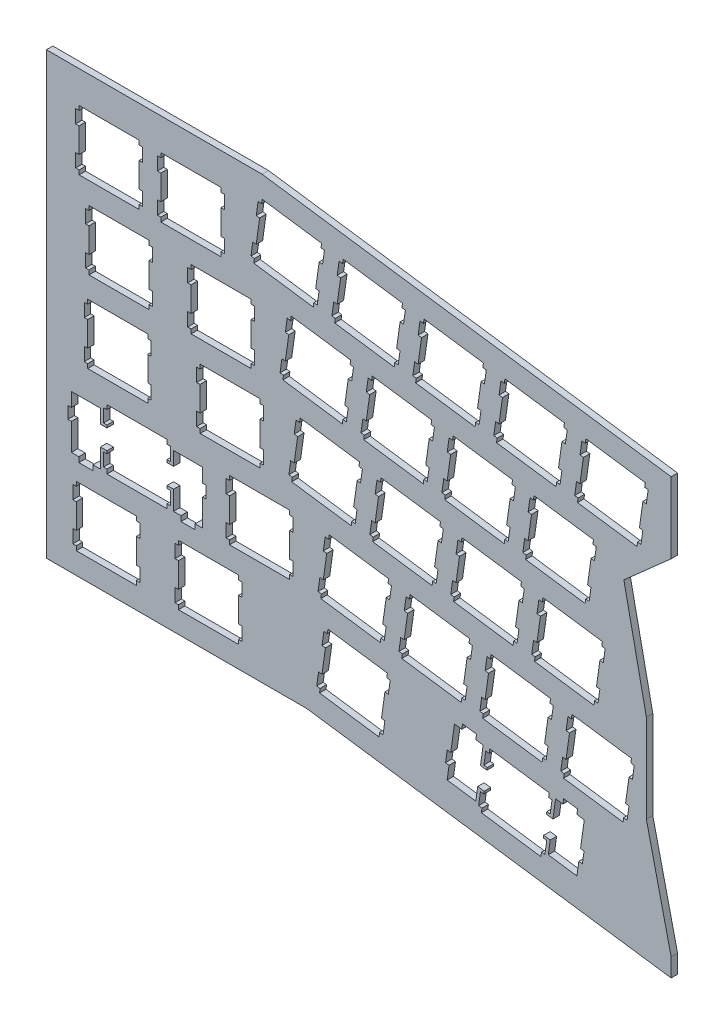
SolidWorks part; units mm, degrees
ref_plane "Front Plane" through (0, 0, 0) normal (0, 0, 1) x (1, 0, 0)
ref_plane "Top Plane" through (0, 0, 0) normal (0, 1, 0) x (1, 0, 0)
ref_plane "Right Plane" through (0, 0, 0) normal (1, 0, 0) x (0, 0, -1)
sketch "Sketch1" plane through (0, 0, 0) normal (0, 0, 1) x (1, 0, 0)
  line L11 (139.4395, -12.6376) -> (133.6626, 12.255)
  line L12 (133.6626, 12.255) -> (133.6626, 32.8822)
  line L13 (133.6626, 32.8822) -> (128.4244, 57.924)
  line L14 (128.4244, 57.924) -> (139.4395, 67.6802)
  line L15 (139.4395, 67.6802) -> (139.4395, 84.2488)
  line L16 (139.4395, 84.2488) -> (44.1124, 97.6439)
  line L17 (44.1124, 97.6439) -> (-6.1561, 97.6439)
  line L18 (-6.1561, 97.6439) -> (-6.1561, -5)
  line L19 (-6.1561, -5) -> (54.5377, -5)
  line L20 (54.5377, -5) -> (139.4395, -16.9252)
  line L21 (139.4395, -16.9252) -> (139.4395, -12.6376)
  line L22 (139.4395, -12.6376) -> (133.6626, 12.255)
  line L23 (133.6626, 12.255) -> (133.6626, 32.8822)
  line L24 (133.6626, 32.8822) -> (128.4244, 57.924)
  line L25 (128.4244, 57.924) -> (139.4395, 67.6802)
  line L26 (139.4395, 67.6802) -> (139.4395, 84.2488)
  line L27 (139.4395, 84.2488) -> (44.1124, 97.6439)
  line L28 (44.1124, 97.6439) -> (-6.1561, 97.6439)
  line L29 (-6.1561, 97.6439) -> (-6.1561, -5)
  line L30 (-6.1561, -5) -> (54.5377, -5)
  line L31 (54.5377, -5) -> (139.4395, -16.9252)
  line L32 (139.4395, -16.9252) -> (139.4395, -12.6376)
  dimension "D1" = 0
extrude "Boss-Extrude1" add sketch "Sketch1" along normal blind 1.5
sketch "Sketch2" plane through (0, 0, 0) normal (0, 0, 1) x (1, 0, 0)
  line L220 (17.4655, 52.0962) -> (3.4669, 52.0962)
  line L221 (3.4669, 52.0962) -> (3.4669, 51.0971)
  line L222 (3.4669, 51.0971) -> (2.6663, 51.0971)
  line L223 (2.6663, 51.0971) -> (2.6663, 47.9968)
  line L224 (2.6663, 47.9968) -> (3.4669, 47.9968)
  line L225 (3.4669, 47.9968) -> (3.4669, 42.1971)
  line L226 (3.4669, 42.1971) -> (2.6663, 42.1971)
  line L227 (2.6663, 42.1971) -> (2.6663, 39.0982)
  line L228 (2.6663, 39.0982) -> (3.4669, 39.0982)
  line L229 (3.4669, 39.0982) -> (3.4669, 38.0977)
  line L230 (3.4669, 38.0977) -> (17.4655, 38.0977)
  line L231 (17.4655, 38.0977) -> (17.4655, 39.0982)
  line L232 (17.4655, 39.0982) -> (18.2648, 39.0982)
  line L233 (18.2648, 39.0982) -> (18.2648, 42.1971)
  line L234 (18.2648, 42.1971) -> (17.4655, 42.1971)
  line L235 (17.4655, 42.1971) -> (17.4655, 47.9968)
  line L236 (17.4655, 47.9968) -> (18.2648, 47.9968)
  line L237 (18.2648, 47.9968) -> (18.2648, 51.0971)
  line L238 (18.2648, 51.0971) -> (17.4655, 51.0971)
  line L239 (17.4655, 51.0971) -> (17.4655, 52.0962)
  line L240 (17.4655, 52.0962) -> (3.4669, 52.0962)
  line L241 (3.4669, 52.0962) -> (3.4669, 51.0971)
  line L242 (3.4669, 51.0971) -> (2.6663, 51.0971)
  line L243 (2.6663, 51.0971) -> (2.6663, 47.9968)
  line L244 (2.6663, 47.9968) -> (3.4669, 47.9968)
  line L245 (3.4669, 47.9968) -> (3.4669, 42.1971)
  line L246 (3.4669, 42.1971) -> (2.6663, 42.1971)
  line L247 (2.6663, 42.1971) -> (2.6663, 39.0982)
  line L248 (2.6663, 39.0982) -> (3.4669, 39.0982)
  line L249 (3.4669, 39.0982) -> (3.4669, 38.0977)
  line L250 (3.4669, 38.0977) -> (17.4655, 38.0977)
  line L251 (17.4655, 38.0977) -> (17.4655, 39.0982)
  line L252 (17.4655, 39.0982) -> (18.2648, 39.0982)
  line L253 (18.2648, 39.0982) -> (18.2648, 42.1971)
  line L254 (18.2648, 42.1971) -> (17.4655, 42.1971)
  line L255 (17.4655, 42.1971) -> (17.4655, 47.9968)
  line L256 (17.4655, 47.9968) -> (18.2648, 47.9968)
  line L257 (18.2648, 47.9968) -> (18.2648, 51.0971)
  line L258 (18.2648, 51.0971) -> (17.4655, 51.0971)
  line L259 (17.4655, 51.0971) -> (17.4655, 52.0962)
  line L420 (123.2716, 41.989) -> (123.4106, 42.9798)
  line L421 (123.4106, 42.9798) -> (109.5484, 44.9267)
  line L422 (109.5484, 44.9267) -> (109.4094, 43.9376)
  line L423 (109.4094, 43.9376) -> (108.6155, 44.0477)
  line L424 (108.6155, 44.0477) -> (108.1845, 40.9791)
  line L425 (108.1845, 40.9791) -> (108.9764, 40.8673)
  line L426 (108.9764, 40.8673) -> (108.1705, 35.1254)
  line L427 (108.1705, 35.1254) -> (107.3785, 35.2358)
  line L428 (107.3785, 35.2358) -> (106.9456, 32.1654)
  line L429 (106.9456, 32.1654) -> (107.7395, 32.0554)
  line L430 (107.7395, 32.0554) -> (107.5985, 31.0645)
  line L431 (107.5985, 31.0645) -> (121.4627, 29.1162)
  line L432 (121.4627, 29.1162) -> (121.6017, 30.1057)
  line L433 (121.6017, 30.1057) -> (122.3936, 29.9953)
  line L434 (122.3936, 29.9953) -> (122.8256, 33.0653)
  line L435 (122.8256, 33.0653) -> (122.0326, 33.1757)
  line L436 (122.0326, 33.1757) -> (122.8406, 38.919)
  line L437 (122.8406, 38.919) -> (123.6325, 38.8075)
  line L438 (123.6325, 38.8075) -> (124.0635, 41.8775)
  line L439 (124.0635, 41.8775) -> (123.2716, 41.989)
  line L440 (123.2716, 41.989) -> (123.4106, 42.9798)
  line L441 (123.4106, 42.9798) -> (109.5484, 44.9267)
  line L442 (109.5484, 44.9267) -> (109.4094, 43.9376)
  line L443 (109.4094, 43.9376) -> (108.6155, 44.0477)
  line L444 (108.6155, 44.0477) -> (108.1845, 40.9791)
  line L445 (108.1845, 40.9791) -> (108.9764, 40.8673)
  line L446 (108.9764, 40.8673) -> (108.1705, 35.1254)
  line L447 (108.1705, 35.1254) -> (107.3785, 35.2358)
  line L448 (107.3785, 35.2358) -> (106.9456, 32.1654)
  line L449 (106.9456, 32.1654) -> (107.7395, 32.0554)
  line L450 (107.7395, 32.0554) -> (107.5985, 31.0645)
  line L451 (107.5985, 31.0645) -> (121.4627, 29.1162)
  line L452 (121.4627, 29.1162) -> (121.6017, 30.1057)
  line L453 (121.6017, 30.1057) -> (122.3936, 29.9953)
  line L454 (122.3936, 29.9953) -> (122.8256, 33.0653)
  line L455 (122.8256, 33.0653) -> (122.0326, 33.1757)
  line L456 (122.0326, 33.1757) -> (122.8406, 38.919)
  line L457 (122.8406, 38.919) -> (123.6325, 38.8075)
  line L458 (123.6325, 38.8075) -> (124.0635, 41.8775)
  line L459 (124.0635, 41.8775) -> (123.2716, 41.989)
  line L500 (50.7872, 43.189) -> (50.3558, 40.119)
  line L501 (50.3558, 40.119) -> (51.148, 40.009)
  line L502 (51.148, 40.009) -> (51.0091, 39.0181)
  line L503 (51.0091, 39.0181) -> (64.8714, 37.0698)
  line L504 (64.8714, 37.0698) -> (65.0103, 38.0589)
  line L505 (65.0103, 38.0589) -> (65.804, 37.9488)
  line L506 (65.804, 37.9488) -> (66.234, 41.019)
  line L507 (66.234, 41.019) -> (65.4432, 41.1293)
  line L508 (65.4432, 41.1293) -> (66.2492, 46.8726)
  line L509 (66.2492, 46.8726) -> (67.0415, 46.7607)
  line L510 (67.0415, 46.7607) -> (67.4743, 49.8311)
  line L511 (67.4743, 49.8311) -> (66.6821, 49.9412)
  line L512 (66.6821, 49.9412) -> (66.8211, 50.9334)
  line L513 (66.8211, 50.9334) -> (52.9573, 52.8803)
  line L514 (52.9573, 52.8803) -> (52.8183, 51.8909)
  line L515 (52.8183, 51.8909) -> (52.0261, 52.0013)
  line L516 (52.0261, 52.0013) -> (51.5932, 48.9327)
  line L517 (51.5932, 48.9327) -> (52.387, 48.8208)
  line L518 (52.387, 48.8208) -> (51.5781, 43.0776)
  line L519 (51.5781, 43.0776) -> (50.7872, 43.189)
  line L520 (50.7872, 43.189) -> (50.3558, 40.119)
  line L521 (50.3558, 40.119) -> (51.148, 40.009)
  line L522 (51.148, 40.009) -> (51.0091, 39.0181)
  line L523 (51.0091, 39.0181) -> (64.8714, 37.0698)
  line L524 (64.8714, 37.0698) -> (65.0103, 38.0589)
  line L525 (65.0103, 38.0589) -> (65.804, 37.9488)
  line L526 (65.804, 37.9488) -> (66.234, 41.019)
  line L527 (66.234, 41.019) -> (65.4432, 41.1293)
  line L528 (65.4432, 41.1293) -> (66.2492, 46.8726)
  line L529 (66.2492, 46.8726) -> (67.0415, 46.7607)
  line L530 (67.0415, 46.7607) -> (67.4743, 49.8311)
  line L531 (67.4743, 49.8311) -> (66.6821, 49.9412)
  line L532 (66.6821, 49.9412) -> (66.8211, 50.9334)
  line L533 (66.8211, 50.9334) -> (52.9573, 52.8803)
  line L534 (52.9573, 52.8803) -> (52.8183, 51.8909)
  line L535 (52.8183, 51.8909) -> (52.0261, 52.0013)
  line L536 (52.0261, 52.0013) -> (51.5932, 48.9327)
  line L537 (51.5932, 48.9327) -> (52.387, 48.8208)
  line L538 (52.387, 48.8208) -> (51.5781, 43.0776)
  line L539 (51.5781, 43.0776) -> (50.7872, 43.189)
  line L740 (103.5298, 32.6466) -> (103.9608, 35.7152)
  line L741 (103.9608, 35.7152) -> (103.1688, 35.8267)
  line L742 (103.1688, 35.8267) -> (103.9758, 41.5703)
  line L743 (103.9758, 41.5703) -> (104.7697, 41.4598)
  line L744 (104.7697, 41.4598) -> (105.1997, 44.5284)
  line L745 (105.1997, 44.5284) -> (104.4087, 44.6403)
  line L746 (104.4087, 44.6403) -> (104.5467, 45.6295)
  line L747 (104.5467, 45.6295) -> (90.6843, 47.578)
  line L748 (90.6843, 47.578) -> (90.5453, 46.5886)
  line L749 (90.5453, 46.5886) -> (89.7529, 46.7004)
  line L750 (89.7529, 46.7004) -> (89.3216, 43.63)
  line L751 (89.3216, 43.63) -> (90.1138, 43.5185)
  line L752 (90.1138, 43.5185) -> (89.3064, 37.7754)
  line L753 (89.3064, 37.7754) -> (88.5141, 37.8867)
  line L754 (88.5141, 37.8867) -> (88.0826, 34.8167)
  line L755 (88.0826, 34.8167) -> (88.8753, 34.7052)
  line L756 (88.8753, 34.7052) -> (88.736, 33.7158)
  line L757 (88.736, 33.7158) -> (102.5998, 31.7675)
  line L758 (102.5998, 31.7675) -> (102.7388, 32.7581)
  line L759 (102.7388, 32.7581) -> (103.5298, 32.6466)
  line L760 (103.5298, 32.6466) -> (103.9608, 35.7152)
  line L761 (103.9608, 35.7152) -> (103.1688, 35.8267)
  line L762 (103.1688, 35.8267) -> (103.9758, 41.5703)
  line L763 (103.9758, 41.5703) -> (104.7697, 41.4598)
  line L764 (104.7697, 41.4598) -> (105.1997, 44.5284)
  line L765 (105.1997, 44.5284) -> (104.4087, 44.6403)
  line L766 (104.4087, 44.6403) -> (104.5467, 45.6295)
  line L767 (104.5467, 45.6295) -> (90.6843, 47.578)
  line L768 (90.6843, 47.578) -> (90.5453, 46.5886)
  line L769 (90.5453, 46.5886) -> (89.7529, 46.7004)
  line L770 (89.7529, 46.7004) -> (89.3216, 43.63)
  line L771 (89.3216, 43.63) -> (90.1138, 43.5185)
  line L772 (90.1138, 43.5185) -> (89.3064, 37.7754)
  line L773 (89.3064, 37.7754) -> (88.5141, 37.8867)
  line L774 (88.5141, 37.8867) -> (88.0826, 34.8167)
  line L775 (88.0826, 34.8167) -> (88.8753, 34.7052)
  line L776 (88.8753, 34.7052) -> (88.736, 33.7158)
  line L777 (88.736, 33.7158) -> (102.5998, 31.7675)
  line L778 (102.5998, 31.7675) -> (102.7388, 32.7581)
  line L779 (102.7388, 32.7581) -> (103.5298, 32.6466)
  line L780 (96.8952, 23.3304) -> (96.0872, 17.5868)
  line L781 (96.0872, 17.5868) -> (95.2953, 17.6985)
  line L782 (95.2953, 17.6985) -> (94.8633, 14.6284)
  line L783 (94.8633, 14.6284) -> (95.6563, 14.5168)
  line L784 (95.6563, 14.5168) -> (95.5173, 13.5275)
  line L785 (95.5173, 13.5275) -> (109.3804, 11.5776)
  line L786 (109.3804, 11.5776) -> (109.5184, 12.5684)
  line L787 (109.5184, 12.5684) -> (110.3104, 12.4567)
  line L788 (110.3104, 12.4567) -> (110.7423, 15.5268)
  line L789 (110.7423, 15.5268) -> (109.9494, 15.6384)
  line L790 (109.9494, 15.6384) -> (110.7573, 21.3818)
  line L791 (110.7573, 21.3818) -> (111.5493, 21.2701)
  line L792 (111.5493, 21.2701) -> (111.9813, 24.3389)
  line L793 (111.9813, 24.3389) -> (111.1883, 24.4517)
  line L794 (111.1883, 24.4517) -> (111.3273, 25.4412)
  line L795 (111.3273, 25.4412) -> (97.4652, 27.3895)
  line L796 (97.4652, 27.3895) -> (97.3262, 26.399)
  line L797 (97.3262, 26.399) -> (96.5342, 26.5105)
  line L798 (96.5342, 26.5105) -> (96.1012, 23.4417)
  line L799 (96.1012, 23.4417) -> (96.8952, 23.3304)
  line L800 (96.8952, 23.3304) -> (96.0872, 17.5868)
  line L801 (96.0872, 17.5868) -> (95.2953, 17.6985)
  line L802 (95.2953, 17.6985) -> (94.8633, 14.6284)
  line L803 (94.8633, 14.6284) -> (95.6563, 14.5168)
  line L804 (95.6563, 14.5168) -> (95.5173, 13.5275)
  line L805 (95.5173, 13.5275) -> (109.3804, 11.5776)
  line L806 (109.3804, 11.5776) -> (109.5184, 12.5684)
  line L807 (109.5184, 12.5684) -> (110.3104, 12.4567)
  line L808 (110.3104, 12.4567) -> (110.7423, 15.5268)
  line L809 (110.7423, 15.5268) -> (109.9494, 15.6384)
  line L810 (109.9494, 15.6384) -> (110.7573, 21.3818)
  line L811 (110.7573, 21.3818) -> (111.5493, 21.2701)
  line L812 (111.5493, 21.2701) -> (111.9813, 24.3389)
  line L813 (111.9813, 24.3389) -> (111.1883, 24.4517)
  line L814 (111.1883, 24.4517) -> (111.3273, 25.4412)
  line L815 (111.3273, 25.4412) -> (97.4652, 27.3895)
  line L816 (97.4652, 27.3895) -> (97.3262, 26.399)
  line L817 (97.3262, 26.399) -> (96.5342, 26.5105)
  line L818 (96.5342, 26.5105) -> (96.1012, 23.4417)
  line L819 (96.1012, 23.4417) -> (96.8952, 23.3304)
  line L860 (15.5985, 12.9997) -> (14.7992, 12.9997)
  line L861 (14.7992, 12.9997) -> (14.7992, 13.9986)
  line L862 (14.7992, 13.9986) -> (0.7992, 13.9986)
  line L863 (0.7992, 13.9986) -> (0.7992, 12.9997)
  line L864 (0.7992, 12.9997) -> (0, 12.9997)
  line L865 (0, 12.9997) -> (0, 9.8993)
  line L866 (0, 9.8993) -> (0.7992, 9.8993)
  line L867 (0.7992, 9.8993) -> (0.7992, 4.0994)
  line L868 (0.7992, 4.0994) -> (0, 4.0994)
  line L869 (0, 4.0994) -> (0, 1.0004)
  line L870 (0, 1.0004) -> (0.7992, 1.0004)
  line L871 (0.7992, 1.0004) -> (0.7992, 0)
  line L872 (0.7992, 0) -> (14.7992, 0)
  line L873 (14.7992, 0) -> (14.7992, 1.0004)
  line L874 (14.7992, 1.0004) -> (15.5985, 1.0004)
  line L875 (15.5985, 1.0004) -> (15.5985, 4.0994)
  line L876 (15.5985, 4.0994) -> (14.7992, 4.0994)
  line L877 (14.7992, 4.0994) -> (14.7992, 9.8993)
  line L878 (14.7992, 9.8993) -> (15.5985, 9.8993)
  line L879 (15.5985, 9.8993) -> (15.5985, 12.9997)
  line L880 (15.5985, 12.9997) -> (14.7992, 12.9997)
  line L881 (14.7992, 12.9997) -> (14.7992, 13.9986)
  line L882 (14.7992, 13.9986) -> (0.7992, 13.9986)
  line L883 (0.7992, 13.9986) -> (0.7992, 12.9997)
  line L884 (0.7992, 12.9997) -> (0, 12.9997)
  line L885 (0, 12.9997) -> (0, 9.8993)
  line L886 (0, 9.8993) -> (0.7992, 9.8993)
  line L887 (0.7992, 9.8993) -> (0.7992, 4.0994)
  line L888 (0.7992, 4.0994) -> (0, 4.0994)
  line L889 (0, 4.0994) -> (0, 1.0004)
  line L890 (0, 1.0004) -> (0.7992, 1.0004)
  line L891 (0.7992, 1.0004) -> (0.7992, 0)
  line L892 (0.7992, 0) -> (14.7992, 0)
  line L893 (14.7992, 0) -> (14.7992, 1.0004)
  line L894 (14.7992, 1.0004) -> (15.5985, 1.0004)
  line L895 (15.5985, 1.0004) -> (15.5985, 4.0994)
  line L896 (15.5985, 4.0994) -> (14.7992, 4.0994)
  line L897 (14.7992, 4.0994) -> (14.7992, 9.8993)
  line L898 (14.7992, 9.8993) -> (15.5985, 9.8993)
  line L899 (15.5985, 9.8993) -> (15.5985, 12.9997)
  line L900 (93.7544, 71.4826) -> (93.8924, 72.472)
  line L901 (93.8924, 72.472) -> (94.6843, 72.362)
  line L902 (94.6843, 72.362) -> (95.1163, 75.432)
  line L903 (95.1163, 75.432) -> (94.3234, 75.5421)
  line L904 (94.3234, 75.5421) -> (95.1313, 81.2856)
  line L905 (95.1313, 81.2856) -> (95.9233, 81.1739)
  line L906 (95.9233, 81.1739) -> (96.3552, 84.2439)
  line L907 (96.3552, 84.2439) -> (95.5623, 84.3543)
  line L908 (95.5623, 84.3543) -> (95.7013, 85.3462)
  line L909 (95.7013, 85.3462) -> (81.8378, 87.2934)
  line L910 (81.8378, 87.2934) -> (81.7002, 86.3039)
  line L911 (81.7002, 86.3039) -> (80.908, 86.4143)
  line L912 (80.908, 86.4143) -> (80.4751, 83.344)
  line L913 (80.4751, 83.344) -> (81.2689, 83.2339)
  line L914 (81.2689, 83.2339) -> (80.4614, 77.4907)
  line L915 (80.4614, 77.4907) -> (79.6691, 77.6022)
  line L916 (79.6691, 77.6022) -> (79.2377, 74.5322)
  line L917 (79.2377, 74.5322) -> (80.0299, 74.4221)
  line L918 (80.0299, 74.4221) -> (79.891, 73.4297)
  line L919 (79.891, 73.4297) -> (93.7544, 71.4826)
  line L920 (93.7544, 71.4826) -> (93.8924, 72.472)
  line L921 (93.8924, 72.472) -> (94.6843, 72.362)
  line L922 (94.6843, 72.362) -> (95.1163, 75.432)
  line L923 (95.1163, 75.432) -> (94.3234, 75.5421)
  line L924 (94.3234, 75.5421) -> (95.1313, 81.2856)
  line L925 (95.1313, 81.2856) -> (95.9233, 81.1739)
  line L926 (95.9233, 81.1739) -> (96.3552, 84.2439)
  line L927 (96.3552, 84.2439) -> (95.5623, 84.3543)
  line L928 (95.5623, 84.3543) -> (95.7013, 85.3462)
  line L929 (95.7013, 85.3462) -> (81.8378, 87.2934)
  line L930 (81.8378, 87.2934) -> (81.7002, 86.3039)
  line L931 (81.7002, 86.3039) -> (80.908, 86.4143)
  line L932 (80.908, 86.4143) -> (80.4751, 83.344)
  line L933 (80.4751, 83.344) -> (81.2689, 83.2339)
  line L934 (81.2689, 83.2339) -> (80.4614, 77.4907)
  line L935 (80.4614, 77.4907) -> (79.6691, 77.6022)
  line L936 (79.6691, 77.6022) -> (79.2377, 74.5322)
  line L937 (79.2377, 74.5322) -> (80.0299, 74.4221)
  line L938 (80.0299, 74.4221) -> (79.891, 73.4297)
  line L939 (79.891, 73.4297) -> (93.7544, 71.4826)
  line L940 (99.771, 83.7645) -> (99.339, 80.6944)
  line L941 (99.339, 80.6944) -> (100.132, 80.5826)
  line L942 (100.132, 80.5826) -> (99.324, 74.8393)
  line L943 (99.324, 74.8393) -> (98.5331, 74.9512)
  line L944 (98.5331, 74.9512) -> (98.1001, 71.8808)
  line L945 (98.1001, 71.8808) -> (98.8931, 71.7693)
  line L946 (98.8931, 71.7693) -> (98.7531, 70.7799)
  line L947 (98.7531, 70.7799) -> (112.6172, 68.8316)
  line L948 (112.6172, 68.8316) -> (112.7552, 69.8222)
  line L949 (112.7552, 69.8222) -> (113.5492, 69.7107)
  line L950 (113.5492, 69.7107) -> (113.9801, 72.7793)
  line L951 (113.9801, 72.7793) -> (113.1872, 72.8911)
  line L952 (113.1872, 72.8911) -> (113.9951, 78.6343)
  line L953 (113.9951, 78.6343) -> (114.7861, 78.5239)
  line L954 (114.7861, 78.5239) -> (115.2191, 81.5929)
  line L955 (115.2191, 81.5929) -> (114.4251, 81.7043)
  line L956 (114.4251, 81.7043) -> (114.5661, 82.6939)
  line L957 (114.5661, 82.6939) -> (100.702, 84.6421)
  line L958 (100.702, 84.6421) -> (100.563, 83.6526)
  line L959 (100.563, 83.6526) -> (99.771, 83.7645)
  line L960 (99.771, 83.7645) -> (99.339, 80.6944)
  line L961 (99.339, 80.6944) -> (100.132, 80.5826)
  line L962 (100.132, 80.5826) -> (99.324, 74.8393)
  line L963 (99.324, 74.8393) -> (98.5331, 74.9512)
  line L964 (98.5331, 74.9512) -> (98.1001, 71.8808)
  line L965 (98.1001, 71.8808) -> (98.8931, 71.7693)
  line L966 (98.8931, 71.7693) -> (98.7531, 70.7799)
  line L967 (98.7531, 70.7799) -> (112.6172, 68.8316)
  line L968 (112.6172, 68.8316) -> (112.7552, 69.8222)
  line L969 (112.7552, 69.8222) -> (113.5492, 69.7107)
  line L970 (113.5492, 69.7107) -> (113.9801, 72.7793)
  line L971 (113.9801, 72.7793) -> (113.1872, 72.8911)
  line L972 (113.1872, 72.8911) -> (113.9951, 78.6343)
  line L973 (113.9951, 78.6343) -> (114.7861, 78.5239)
  line L974 (114.7861, 78.5239) -> (115.2191, 81.5929)
  line L975 (115.2191, 81.5929) -> (114.4251, 81.7043)
  line L976 (114.4251, 81.7043) -> (114.5661, 82.6939)
  line L977 (114.5661, 82.6939) -> (100.702, 84.6421)
  line L978 (100.702, 84.6421) -> (100.563, 83.6526)
  line L979 (100.563, 83.6526) -> (99.771, 83.7645)
  line L980 (90.5163, 14.2288) -> (90.6553, 15.2196)
  line L981 (90.6553, 15.2196) -> (91.4465, 15.108)
  line L982 (91.4465, 15.108) -> (91.8795, 18.178)
  line L983 (91.8795, 18.178) -> (91.0866, 18.2883)
  line L984 (91.0866, 18.2883) -> (91.8945, 24.033)
  line L985 (91.8945, 24.033) -> (92.6865, 23.9212)
  line L986 (92.6865, 23.9212) -> (93.1164, 26.9901)
  line L987 (93.1164, 26.9901) -> (92.3255, 27.1016)
  line L988 (92.3255, 27.1016) -> (92.4635, 28.0926)
  line L989 (92.4635, 28.0926) -> (78.6013, 30.0408)
  line L990 (78.6013, 30.0408) -> (78.4619, 29.0499)
  line L991 (78.4619, 29.0499) -> (77.6697, 29.1617)
  line L992 (77.6697, 29.1617) -> (77.2382, 26.0931)
  line L993 (77.2382, 26.0931) -> (78.0306, 25.9799)
  line L994 (78.0306, 25.9799) -> (77.2245, 20.238)
  line L995 (77.2245, 20.238) -> (76.4322, 20.3482)
  line L996 (76.4322, 20.3482) -> (75.9997, 17.2795)
  line L997 (75.9997, 17.2795) -> (76.792, 17.1679)
  line L998 (76.792, 17.1679) -> (76.6527, 16.1786)
  line L999 (76.6527, 16.1786) -> (90.5163, 14.2288)
  line L1000 (90.5163, 14.2288) -> (90.6553, 15.2196)
  line L1001 (90.6553, 15.2196) -> (91.4465, 15.108)
  line L1002 (91.4465, 15.108) -> (91.8795, 18.178)
  line L1003 (91.8795, 18.178) -> (91.0866, 18.2883)
  line L1004 (91.0866, 18.2883) -> (91.8945, 24.033)
  line L1005 (91.8945, 24.033) -> (92.6865, 23.9212)
  line L1006 (92.6865, 23.9212) -> (93.1164, 26.9901)
  line L1007 (93.1164, 26.9901) -> (92.3255, 27.1016)
  line L1008 (92.3255, 27.1016) -> (92.4635, 28.0926)
  line L1009 (92.4635, 28.0926) -> (78.6013, 30.0408)
  line L1010 (78.6013, 30.0408) -> (78.4619, 29.0499)
  line L1011 (78.4619, 29.0499) -> (77.6697, 29.1617)
  line L1012 (77.6697, 29.1617) -> (77.2382, 26.0931)
  line L1013 (77.2382, 26.0931) -> (78.0306, 25.9799)
  line L1014 (78.0306, 25.9799) -> (77.2245, 20.238)
  line L1015 (77.2245, 20.238) -> (76.4322, 20.3482)
  line L1016 (76.4322, 20.3482) -> (75.9997, 17.2795)
  line L1017 (75.9997, 17.2795) -> (76.792, 17.1679)
  line L1018 (76.792, 17.1679) -> (76.6527, 16.1786)
  line L1019 (76.6527, 16.1786) -> (90.5163, 14.2288)
  line L1060 (23.811, 9.8993) -> (24.6116, 9.8993)
  line L1061 (24.6116, 9.8993) -> (24.6116, 4.0994)
  line L1062 (24.6116, 4.0994) -> (23.811, 4.0994)
  line L1063 (23.811, 4.0994) -> (23.811, 1.0004)
  line L1064 (23.811, 1.0004) -> (24.6116, 1.0004)
  line L1065 (24.6116, 1.0004) -> (24.6116, 0)
  line L1066 (24.6116, 0) -> (38.6101, 0)
  line L1067 (38.6101, 0) -> (38.6101, 1.0004)
  line L1068 (38.6101, 1.0004) -> (39.4109, 1.0004)
  line L1069 (39.4109, 1.0004) -> (39.4109, 4.0994)
  line L1070 (39.4109, 4.0994) -> (38.6101, 4.0994)
  line L1071 (38.6101, 4.0994) -> (38.6101, 9.8993)
  line L1072 (38.6101, 9.8993) -> (39.4109, 9.8993)
  line L1073 (39.4109, 9.8993) -> (39.4109, 12.9997)
  line L1074 (39.4109, 12.9997) -> (38.6101, 12.9997)
  line L1075 (38.6101, 12.9997) -> (38.6101, 13.9986)
  line L1076 (38.6101, 13.9986) -> (24.6116, 13.9986)
  line L1077 (24.6116, 13.9986) -> (24.6116, 12.9997)
  line L1078 (24.6116, 12.9997) -> (23.811, 12.9997)
  line L1079 (23.811, 12.9997) -> (23.811, 9.8993)
  line L1080 (23.811, 9.8993) -> (24.6116, 9.8993)
  line L1081 (24.6116, 9.8993) -> (24.6116, 4.0994)
  line L1082 (24.6116, 4.0994) -> (23.811, 4.0994)
  line L1083 (23.811, 4.0994) -> (23.811, 1.0004)
  line L1084 (23.811, 1.0004) -> (24.6116, 1.0004)
  line L1085 (24.6116, 1.0004) -> (24.6116, 0)
  line L1086 (24.6116, 0) -> (38.6101, 0)
  line L1087 (38.6101, 0) -> (38.6101, 1.0004)
  line L1088 (38.6101, 1.0004) -> (39.4109, 1.0004)
  line L1089 (39.4109, 1.0004) -> (39.4109, 4.0994)
  line L1090 (39.4109, 4.0994) -> (38.6101, 4.0994)
  line L1091 (38.6101, 4.0994) -> (38.6101, 9.8993)
  line L1092 (38.6101, 9.8993) -> (39.4109, 9.8993)
  line L1093 (39.4109, 9.8993) -> (39.4109, 12.9997)
  line L1094 (39.4109, 12.9997) -> (38.6101, 12.9997)
  line L1095 (38.6101, 12.9997) -> (38.6101, 13.9986)
  line L1096 (38.6101, 13.9986) -> (24.6116, 13.9986)
  line L1097 (24.6116, 13.9986) -> (24.6116, 12.9997)
  line L1098 (24.6116, 12.9997) -> (23.811, 12.9997)
  line L1099 (23.811, 12.9997) -> (23.811, 9.8993)
  line L1100 (0.6669, 77.1958) -> (1.4661, 77.1958)
  line L1101 (1.4661, 77.1958) -> (1.4661, 76.1954)
  line L1102 (1.4661, 76.1954) -> (15.4662, 76.1954)
  line L1103 (15.4662, 76.1954) -> (15.4662, 77.1958)
  line L1104 (15.4662, 77.1958) -> (16.2653, 77.1958)
  line L1105 (16.2653, 77.1958) -> (16.2653, 80.2961)
  line L1106 (16.2653, 80.2961) -> (15.4662, 80.2961)
  line L1107 (15.4662, 80.2961) -> (15.4662, 86.0944)
  line L1108 (15.4662, 86.0944) -> (16.2653, 86.0944)
  line L1109 (16.2653, 86.0944) -> (16.2653, 89.1953)
  line L1110 (16.2653, 89.1953) -> (15.4662, 89.1953)
  line L1111 (15.4662, 89.1953) -> (15.4662, 90.1942)
  line L1112 (15.4662, 90.1942) -> (1.4661, 90.1942)
  line L1113 (1.4661, 90.1942) -> (1.4661, 89.1953)
  line L1114 (1.4661, 89.1953) -> (0.6669, 89.1953)
  line L1115 (0.6669, 89.1953) -> (0.6669, 86.0944)
  line L1116 (0.6669, 86.0944) -> (1.4661, 86.0944)
  line L1117 (1.4661, 86.0944) -> (1.4661, 80.2961)
  line L1118 (1.4661, 80.2961) -> (0.6669, 80.2961)
  line L1119 (0.6669, 80.2961) -> (0.6669, 77.1958)
  line L1120 (0.6669, 77.1958) -> (1.4661, 77.1958)
  line L1121 (1.4661, 77.1958) -> (1.4661, 76.1954)
  line L1122 (1.4661, 76.1954) -> (15.4662, 76.1954)
  line L1123 (15.4662, 76.1954) -> (15.4662, 77.1958)
  line L1124 (15.4662, 77.1958) -> (16.2653, 77.1958)
  line L1125 (16.2653, 77.1958) -> (16.2653, 80.2961)
  line L1126 (16.2653, 80.2961) -> (15.4662, 80.2961)
  line L1127 (15.4662, 80.2961) -> (15.4662, 86.0944)
  line L1128 (15.4662, 86.0944) -> (16.2653, 86.0944)
  line L1129 (16.2653, 86.0944) -> (16.2653, 89.1953)
  line L1130 (16.2653, 89.1953) -> (15.4662, 89.1953)
  line L1131 (15.4662, 89.1953) -> (15.4662, 90.1942)
  line L1132 (15.4662, 90.1942) -> (1.4661, 90.1942)
  line L1133 (1.4661, 90.1942) -> (1.4661, 89.1953)
  line L1134 (1.4661, 89.1953) -> (0.6669, 89.1953)
  line L1135 (0.6669, 89.1953) -> (0.6669, 86.0944)
  line L1136 (0.6669, 86.0944) -> (1.4661, 86.0944)
  line L1137 (1.4661, 86.0944) -> (1.4661, 80.2961)
  line L1138 (1.4661, 80.2961) -> (0.6669, 80.2961)
  line L1139 (0.6669, 80.2961) -> (0.6669, 77.1958)
  line L1140 (26.7639, 58.147) -> (27.5646, 58.147)
  line L1141 (27.5646, 58.147) -> (27.5646, 57.1465)
  line L1142 (27.5646, 57.1465) -> (41.563, 57.1465)
  line L1143 (41.563, 57.1465) -> (41.563, 58.147)
  line L1144 (41.563, 58.147) -> (42.3624, 58.147)
  line L1145 (42.3624, 58.147) -> (42.3624, 61.2473)
  line L1146 (42.3624, 61.2473) -> (41.563, 61.2473)
  line L1147 (41.563, 61.2473) -> (41.563, 67.0456)
  line L1148 (41.563, 67.0456) -> (42.3624, 67.0456)
  line L1149 (42.3624, 67.0456) -> (42.3624, 70.1459)
  line L1150 (42.3624, 70.1459) -> (41.563, 70.1459)
  line L1151 (41.563, 70.1459) -> (41.563, 71.145)
  line L1152 (41.563, 71.145) -> (27.5646, 71.145)
  line L1153 (27.5646, 71.145) -> (27.5646, 70.1459)
  line L1154 (27.5646, 70.1459) -> (26.7639, 70.1459)
  line L1155 (26.7639, 70.1459) -> (26.7639, 67.0456)
  line L1156 (26.7639, 67.0456) -> (27.5646, 67.0456)
  line L1157 (27.5646, 67.0456) -> (27.5646, 61.2473)
  line L1158 (27.5646, 61.2473) -> (26.7639, 61.2473)
  line L1159 (26.7639, 61.2473) -> (26.7639, 58.147)
  line L1160 (26.7639, 58.147) -> (27.5646, 58.147)
  line L1161 (27.5646, 58.147) -> (27.5646, 57.1465)
  line L1162 (27.5646, 57.1465) -> (41.563, 57.1465)
  line L1163 (41.563, 57.1465) -> (41.563, 58.147)
  line L1164 (41.563, 58.147) -> (42.3624, 58.147)
  line L1165 (42.3624, 58.147) -> (42.3624, 61.2473)
  line L1166 (42.3624, 61.2473) -> (41.563, 61.2473)
  line L1167 (41.563, 61.2473) -> (41.563, 67.0456)
  line L1168 (41.563, 67.0456) -> (42.3624, 67.0456)
  line L1169 (42.3624, 67.0456) -> (42.3624, 70.1459)
  line L1170 (42.3624, 70.1459) -> (41.563, 70.1459)
  line L1171 (41.563, 70.1459) -> (41.563, 71.145)
  line L1172 (41.563, 71.145) -> (27.5646, 71.145)
  line L1173 (27.5646, 71.145) -> (27.5646, 70.1459)
  line L1174 (27.5646, 70.1459) -> (26.7639, 70.1459)
  line L1175 (26.7639, 70.1459) -> (26.7639, 67.0456)
  line L1176 (26.7639, 67.0456) -> (27.5646, 67.0456)
  line L1177 (27.5646, 67.0456) -> (27.5646, 61.2473)
  line L1178 (27.5646, 61.2473) -> (26.7639, 61.2473)
  line L1179 (26.7639, 61.2473) -> (26.7639, 58.147)
  line L1220 (69.1855, 65.6952) -> (68.3781, 59.9535)
  line L1221 (68.3781, 59.9535) -> (67.5872, 60.0635)
  line L1222 (67.5872, 60.0635) -> (67.1543, 56.9949)
  line L1223 (67.1543, 56.9949) -> (67.9467, 56.8834)
  line L1224 (67.9467, 56.8834) -> (67.8077, 55.8925)
  line L1225 (67.8077, 55.8925) -> (81.6713, 53.9442)
  line L1226 (81.6713, 53.9442) -> (81.8089, 54.9348)
  line L1227 (81.8089, 54.9348) -> (82.6012, 54.8233)
  line L1228 (82.6012, 54.8233) -> (83.0341, 57.8933)
  line L1229 (83.0341, 57.8933) -> (82.2417, 58.0048)
  line L1230 (82.2417, 58.0048) -> (83.0492, 63.7483)
  line L1231 (83.0492, 63.7483) -> (83.8401, 63.6365)
  line L1232 (83.8401, 63.6365) -> (84.2715, 66.7056)
  line L1233 (84.2715, 66.7056) -> (83.4792, 66.817)
  line L1234 (83.4792, 66.817) -> (83.6182, 67.8079)
  line L1235 (83.6182, 67.8079) -> (69.756, 69.7562)
  line L1236 (69.756, 69.7562) -> (69.617, 68.7652)
  line L1237 (69.617, 68.7652) -> (68.8246, 68.8771)
  line L1238 (68.8246, 68.8771) -> (68.3933, 65.8071)
  line L1239 (68.3933, 65.8071) -> (69.1855, 65.6952)
  line L1240 (69.1855, 65.6952) -> (68.3781, 59.9535)
  line L1241 (68.3781, 59.9535) -> (67.5872, 60.0635)
  line L1242 (67.5872, 60.0635) -> (67.1543, 56.9949)
  line L1243 (67.1543, 56.9949) -> (67.9467, 56.8834)
  line L1244 (67.9467, 56.8834) -> (67.8077, 55.8925)
  line L1245 (67.8077, 55.8925) -> (81.6713, 53.9442)
  line L1246 (81.6713, 53.9442) -> (81.8089, 54.9348)
  line L1247 (81.8089, 54.9348) -> (82.6012, 54.8233)
  line L1248 (82.6012, 54.8233) -> (83.0341, 57.8933)
  line L1249 (83.0341, 57.8933) -> (82.2417, 58.0048)
  line L1250 (82.2417, 58.0048) -> (83.0492, 63.7483)
  line L1251 (83.0492, 63.7483) -> (83.8401, 63.6365)
  line L1252 (83.8401, 63.6365) -> (84.2715, 66.7056)
  line L1253 (84.2715, 66.7056) -> (83.4792, 66.817)
  line L1254 (83.4792, 66.817) -> (83.6182, 67.8079)
  line L1255 (83.6182, 67.8079) -> (69.756, 69.7562)
  line L1256 (69.756, 69.7562) -> (69.617, 68.7652)
  line L1257 (69.617, 68.7652) -> (68.8246, 68.8771)
  line L1258 (68.8246, 68.8771) -> (68.3933, 65.8071)
  line L1259 (68.3933, 65.8071) -> (69.1855, 65.6952)
  line L1260 (102.7048, 60.9856) -> (103.1358, 64.0556)
  line L1261 (103.1358, 64.0556) -> (102.3429, 64.1657)
  line L1262 (102.3429, 64.1657) -> (102.4829, 65.1566)
  line L1263 (102.4829, 65.1566) -> (88.6189, 67.1048)
  line L1264 (88.6189, 67.1048) -> (88.4795, 66.1143)
  line L1265 (88.4795, 66.1143) -> (87.6887, 66.2258)
  line L1266 (87.6887, 66.2258) -> (87.2562, 63.1558)
  line L1267 (87.2562, 63.1558) -> (88.0498, 63.0457)
  line L1268 (88.0498, 63.0457) -> (87.241, 57.3007)
  line L1269 (87.241, 57.3007) -> (86.4501, 57.4139)
  line L1270 (86.4501, 57.4139) -> (86.0187, 54.3439)
  line L1271 (86.0187, 54.3439) -> (86.811, 54.2321)
  line L1272 (86.811, 54.2321) -> (86.6716, 53.2416)
  line L1273 (86.6716, 53.2416) -> (100.534, 51.2943)
  line L1274 (100.534, 51.2943) -> (100.673, 52.2839)
  line L1275 (100.673, 52.2839) -> (101.4659, 52.172)
  line L1276 (101.4659, 52.172) -> (101.8969, 55.2421)
  line L1277 (101.8969, 55.2421) -> (101.1049, 55.3539)
  line L1278 (101.1049, 55.3539) -> (101.9119, 61.0957)
  line L1279 (101.9119, 61.0957) -> (102.7048, 60.9856)
  line L1280 (102.7048, 60.9856) -> (103.1358, 64.0556)
  line L1281 (103.1358, 64.0556) -> (102.3429, 64.1657)
  line L1282 (102.3429, 64.1657) -> (102.4829, 65.1566)
  line L1283 (102.4829, 65.1566) -> (88.6189, 67.1048)
  line L1284 (88.6189, 67.1048) -> (88.4795, 66.1143)
  line L1285 (88.4795, 66.1143) -> (87.6887, 66.2258)
  line L1286 (87.6887, 66.2258) -> (87.2562, 63.1558)
  line L1287 (87.2562, 63.1558) -> (88.0498, 63.0457)
  line L1288 (88.0498, 63.0457) -> (87.241, 57.3007)
  line L1289 (87.241, 57.3007) -> (86.4501, 57.4139)
  line L1290 (86.4501, 57.4139) -> (86.0187, 54.3439)
  line L1291 (86.0187, 54.3439) -> (86.811, 54.2321)
  line L1292 (86.811, 54.2321) -> (86.6716, 53.2416)
  line L1293 (86.6716, 53.2416) -> (100.534, 51.2943)
  line L1294 (100.534, 51.2943) -> (100.673, 52.2839)
  line L1295 (100.673, 52.2839) -> (101.4659, 52.172)
  line L1296 (101.4659, 52.172) -> (101.8969, 55.2421)
  line L1297 (101.8969, 55.2421) -> (101.1049, 55.3539)
  line L1298 (101.1049, 55.3539) -> (101.9119, 61.0957)
  line L1299 (101.9119, 61.0957) -> (102.7048, 60.9856)
  line L1300 (106.5516, 63.5748) -> (106.1206, 60.5044)
  line L1301 (106.1206, 60.5044) -> (106.9126, 60.3943)
  line L1302 (106.9126, 60.3943) -> (106.1046, 54.6512)
  line L1303 (106.1046, 54.6512) -> (105.3127, 54.7612)
  line L1304 (105.3127, 54.7612) -> (104.8817, 51.6926)
  line L1305 (104.8817, 51.6926) -> (105.6737, 51.5811)
  line L1306 (105.6737, 51.5811) -> (105.5347, 50.5903)
  line L1307 (105.5347, 50.5903) -> (119.3968, 48.6416)
  line L1308 (119.3968, 48.6416) -> (119.5358, 49.6325)
  line L1309 (119.5358, 49.6325) -> (120.3297, 49.521)
  line L1310 (120.3297, 49.521) -> (120.7597, 52.591)
  line L1311 (120.7597, 52.591) -> (119.9688, 52.7025)
  line L1312 (119.9688, 52.7025) -> (120.7747, 58.4458)
  line L1313 (120.7747, 58.4458) -> (121.5667, 58.3343)
  line L1314 (121.5667, 58.3343) -> (121.9996, 61.4043)
  line L1315 (121.9996, 61.4043) -> (121.2057, 61.5148)
  line L1316 (121.2057, 61.5148) -> (121.3467, 62.5053)
  line L1317 (121.3467, 62.5053) -> (107.4835, 64.4539)
  line L1318 (107.4835, 64.4539) -> (107.3435, 63.463)
  line L1319 (107.3435, 63.463) -> (106.5516, 63.5748)
  line L1320 (106.5516, 63.5748) -> (106.1206, 60.5044)
  line L1321 (106.1206, 60.5044) -> (106.9126, 60.3943)
  line L1322 (106.9126, 60.3943) -> (106.1046, 54.6512)
  line L1323 (106.1046, 54.6512) -> (105.3127, 54.7612)
  line L1324 (105.3127, 54.7612) -> (104.8817, 51.6926)
  line L1325 (104.8817, 51.6926) -> (105.6737, 51.5811)
  line L1326 (105.6737, 51.5811) -> (105.5347, 50.5903)
  line L1327 (105.5347, 50.5903) -> (119.3968, 48.6416)
  line L1328 (119.3968, 48.6416) -> (119.5358, 49.6325)
  line L1329 (119.5358, 49.6325) -> (120.3297, 49.521)
  line L1330 (120.3297, 49.521) -> (120.7597, 52.591)
  line L1331 (120.7597, 52.591) -> (119.9688, 52.7025)
  line L1332 (119.9688, 52.7025) -> (120.7747, 58.4458)
  line L1333 (120.7747, 58.4458) -> (121.5667, 58.3343)
  line L1334 (121.5667, 58.3343) -> (121.9996, 61.4043)
  line L1335 (121.9996, 61.4043) -> (121.2057, 61.5148)
  line L1336 (121.2057, 61.5148) -> (121.3467, 62.5053)
  line L1337 (121.3467, 62.5053) -> (107.4835, 64.4539)
  line L1338 (107.4835, 64.4539) -> (107.3435, 63.463)
  line L1339 (107.3435, 63.463) -> (106.5516, 63.5748)
  line L1380 (84.3057, 38.478) -> (85.1135, 44.2213)
  line L1381 (85.1135, 44.2213) -> (85.9058, 44.1098)
  line L1382 (85.9058, 44.1098) -> (86.3369, 47.1798)
  line L1383 (86.3369, 47.1798) -> (85.5446, 47.2913)
  line L1384 (85.5446, 47.2913) -> (85.6839, 48.2807)
  line L1385 (85.6839, 48.2807) -> (71.8217, 50.229)
  line L1386 (71.8217, 50.229) -> (71.681, 49.2384)
  line L1387 (71.681, 49.2384) -> (70.8886, 49.3513)
  line L1388 (70.8886, 49.3513) -> (70.459, 46.2827)
  line L1389 (70.459, 46.2827) -> (71.2499, 46.1698)
  line L1390 (71.2499, 46.1698) -> (70.4438, 40.4263)
  line L1391 (70.4438, 40.4263) -> (69.6512, 40.5381)
  line L1392 (69.6512, 40.5381) -> (69.2201, 37.4681)
  line L1393 (69.2201, 37.4681) -> (70.011, 37.3563)
  line L1394 (70.011, 37.3563) -> (69.8717, 36.3671)
  line L1395 (69.8717, 36.3671) -> (83.7353, 34.4185)
  line L1396 (83.7353, 34.4185) -> (83.8746, 35.4094)
  line L1397 (83.8746, 35.4094) -> (84.667, 35.2961)
  line L1398 (84.667, 35.2961) -> (85.0983, 38.3665)
  line L1399 (85.0983, 38.3665) -> (84.3057, 38.478)
  line L1400 (84.3057, 38.478) -> (85.1135, 44.2213)
  line L1401 (85.1135, 44.2213) -> (85.9058, 44.1098)
  line L1402 (85.9058, 44.1098) -> (86.3369, 47.1798)
  line L1403 (86.3369, 47.1798) -> (85.5446, 47.2913)
  line L1404 (85.5446, 47.2913) -> (85.6839, 48.2807)
  line L1405 (85.6839, 48.2807) -> (71.8217, 50.229)
  line L1406 (71.8217, 50.229) -> (71.681, 49.2384)
  line L1407 (71.681, 49.2384) -> (70.8886, 49.3513)
  line L1408 (70.8886, 49.3513) -> (70.459, 46.2827)
  line L1409 (70.459, 46.2827) -> (71.2499, 46.1698)
  line L1410 (71.2499, 46.1698) -> (70.4438, 40.4263)
  line L1411 (70.4438, 40.4263) -> (69.6512, 40.5381)
  line L1412 (69.6512, 40.5381) -> (69.2201, 37.4681)
  line L1413 (69.2201, 37.4681) -> (70.011, 37.3563)
  line L1414 (70.011, 37.3563) -> (69.8717, 36.3671)
  line L1415 (69.8717, 36.3671) -> (83.7353, 34.4185)
  line L1416 (83.7353, 34.4185) -> (83.8746, 35.4094)
  line L1417 (83.8746, 35.4094) -> (84.667, 35.2961)
  line L1418 (84.667, 35.2961) -> (85.0983, 38.3665)
  line L1419 (85.0983, 38.3665) -> (84.3057, 38.478)
  line L1420 (35.7164, 20.0493) -> (36.5172, 20.0493)
  line L1421 (36.5172, 20.0493) -> (36.5172, 19.0488)
  line L1422 (36.5172, 19.0488) -> (50.5156, 19.0488)
  line L1423 (50.5156, 19.0488) -> (50.5156, 20.0493)
  line L1424 (50.5156, 20.0493) -> (51.3149, 20.0493)
  line L1425 (51.3149, 20.0493) -> (51.3149, 23.1483)
  line L1426 (51.3149, 23.1483) -> (50.5156, 23.1483)
  line L1427 (50.5156, 23.1483) -> (50.5156, 28.948)
  line L1428 (50.5156, 28.948) -> (51.3149, 28.948)
  line L1429 (51.3149, 28.948) -> (51.3149, 32.0483)
  line L1430 (51.3149, 32.0483) -> (50.5156, 32.0483)
  line L1431 (50.5156, 32.0483) -> (50.5156, 33.0473)
  line L1432 (50.5156, 33.0473) -> (36.5172, 33.0473)
  line L1433 (36.5172, 33.0473) -> (36.5172, 32.0483)
  line L1434 (36.5172, 32.0483) -> (35.7164, 32.0483)
  line L1435 (35.7164, 32.0483) -> (35.7164, 28.948)
  line L1436 (35.7164, 28.948) -> (36.5172, 28.948)
  line L1437 (36.5172, 28.948) -> (36.5172, 23.1483)
  line L1438 (36.5172, 23.1483) -> (35.7164, 23.1483)
  line L1439 (35.7164, 23.1483) -> (35.7164, 20.0493)
  line L1440 (35.7164, 20.0493) -> (36.5172, 20.0493)
  line L1441 (36.5172, 20.0493) -> (36.5172, 19.0488)
  line L1442 (36.5172, 19.0488) -> (50.5156, 19.0488)
  line L1443 (50.5156, 19.0488) -> (50.5156, 20.0493)
  line L1444 (50.5156, 20.0493) -> (51.3149, 20.0493)
  line L1445 (51.3149, 20.0493) -> (51.3149, 23.1483)
  line L1446 (51.3149, 23.1483) -> (50.5156, 23.1483)
  line L1447 (50.5156, 23.1483) -> (50.5156, 28.948)
  line L1448 (50.5156, 28.948) -> (51.3149, 28.948)
  line L1449 (51.3149, 28.948) -> (51.3149, 32.0483)
  line L1450 (51.3149, 32.0483) -> (50.5156, 32.0483)
  line L1451 (50.5156, 32.0483) -> (50.5156, 33.0473)
  line L1452 (50.5156, 33.0473) -> (36.5172, 33.0473)
  line L1453 (36.5172, 33.0473) -> (36.5172, 32.0483)
  line L1454 (36.5172, 32.0483) -> (35.7164, 32.0483)
  line L1455 (35.7164, 32.0483) -> (35.7164, 28.948)
  line L1456 (35.7164, 28.948) -> (36.5172, 28.948)
  line L1457 (36.5172, 28.948) -> (36.5172, 23.1483)
  line L1458 (36.5172, 23.1483) -> (35.7164, 23.1483)
  line L1459 (35.7164, 23.1483) -> (35.7164, 20.0493)
  line L1460 (72.5836, 17.7605) -> (73.0151, 20.8292)
  line L1461 (73.0151, 20.8292) -> (72.2227, 20.9408)
  line L1462 (72.2227, 20.9408) -> (73.0303, 26.6825)
  line L1463 (73.0303, 26.6825) -> (73.8225, 26.5724)
  line L1464 (73.8225, 26.5724) -> (74.2536, 29.6426)
  line L1465 (74.2536, 29.6426) -> (73.4628, 29.753)
  line L1466 (73.4628, 29.753) -> (73.6006, 30.7435)
  line L1467 (73.6006, 30.7435) -> (59.7384, 32.6921)
  line L1468 (59.7384, 32.6921) -> (59.599, 31.7012)
  line L1469 (59.599, 31.7012) -> (58.8068, 31.8127)
  line L1470 (58.8068, 31.8127) -> (58.3757, 28.7426)
  line L1471 (58.3757, 28.7426) -> (59.1665, 28.6326)
  line L1472 (59.1665, 28.6326) -> (58.3605, 22.8894)
  line L1473 (58.3605, 22.8894) -> (57.5682, 22.9995)
  line L1474 (57.5682, 22.9995) -> (57.1368, 19.9308)
  line L1475 (57.1368, 19.9308) -> (57.9291, 19.8192)
  line L1476 (57.9291, 19.8192) -> (57.7897, 18.8283)
  line L1477 (57.7897, 18.8283) -> (71.652, 16.8814)
  line L1478 (71.652, 16.8814) -> (71.7928, 17.8707)
  line L1479 (71.7928, 17.8707) -> (72.5836, 17.7605)
  line L1480 (72.5836, 17.7605) -> (73.0151, 20.8292)
  line L1481 (73.0151, 20.8292) -> (72.2227, 20.9408)
  line L1482 (72.2227, 20.9408) -> (73.0303, 26.6825)
  line L1483 (73.0303, 26.6825) -> (73.8225, 26.5724)
  line L1484 (73.8225, 26.5724) -> (74.2536, 29.6426)
  line L1485 (74.2536, 29.6426) -> (73.4628, 29.753)
  line L1486 (73.4628, 29.753) -> (73.6006, 30.7435)
  line L1487 (73.6006, 30.7435) -> (59.7384, 32.6921)
  line L1488 (59.7384, 32.6921) -> (59.599, 31.7012)
  line L1489 (59.599, 31.7012) -> (58.8068, 31.8127)
  line L1490 (58.8068, 31.8127) -> (58.3757, 28.7426)
  line L1491 (58.3757, 28.7426) -> (59.1665, 28.6326)
  line L1492 (59.1665, 28.6326) -> (58.3605, 22.8894)
  line L1493 (58.3605, 22.8894) -> (57.5682, 22.9995)
  line L1494 (57.5682, 22.9995) -> (57.1368, 19.9308)
  line L1495 (57.1368, 19.9308) -> (57.9291, 19.8192)
  line L1496 (57.9291, 19.8192) -> (57.7897, 18.8283)
  line L1497 (57.7897, 18.8283) -> (71.652, 16.8814)
  line L1498 (71.652, 16.8814) -> (71.7928, 17.8707)
  line L1499 (71.7928, 17.8707) -> (72.5836, 17.7605)
  line L1540 (114.1561, 15.0473) -> (113.7262, 11.9773)
  line L1541 (113.7262, 11.9773) -> (114.5201, 11.8657)
  line L1542 (114.5201, 11.8657) -> (114.3791, 10.8748)
  line L1543 (114.3791, 10.8748) -> (128.2433, 8.9277)
  line L1544 (128.2433, 8.9277) -> (128.3812, 9.9172)
  line L1545 (128.3812, 9.9172) -> (129.1752, 9.8069)
  line L1546 (129.1752, 9.8069) -> (129.6062, 12.8756)
  line L1547 (129.6062, 12.8756) -> (128.8132, 12.9873)
  line L1548 (128.8132, 12.9873) -> (129.6212, 18.7291)
  line L1549 (129.6212, 18.7291) -> (130.4121, 18.6189)
  line L1550 (130.4121, 18.6189) -> (130.8451, 21.6891)
  line L1551 (130.8451, 21.6891) -> (130.0511, 21.7992)
  line L1552 (130.0511, 21.7992) -> (130.1921, 22.7899)
  line L1553 (130.1921, 22.7899) -> (116.328, 24.7386)
  line L1554 (116.328, 24.7386) -> (116.189, 23.749)
  line L1555 (116.189, 23.749) -> (115.394, 23.8594)
  line L1556 (115.394, 23.8594) -> (114.9651, 20.7892)
  line L1557 (114.9651, 20.7892) -> (115.758, 20.679)
  line L1558 (115.758, 20.679) -> (114.9501, 14.9357)
  line L1559 (114.9501, 14.9357) -> (114.1561, 15.0473)
  line L1560 (114.1561, 15.0473) -> (113.7262, 11.9773)
  line L1561 (113.7262, 11.9773) -> (114.5201, 11.8657)
  line L1562 (114.5201, 11.8657) -> (114.3791, 10.8748)
  line L1563 (114.3791, 10.8748) -> (128.2433, 8.9277)
  line L1564 (128.2433, 8.9277) -> (128.3812, 9.9172)
  line L1565 (128.3812, 9.9172) -> (129.1752, 9.8069)
  line L1566 (129.1752, 9.8069) -> (129.6062, 12.8756)
  line L1567 (129.6062, 12.8756) -> (128.8132, 12.9873)
  line L1568 (128.8132, 12.9873) -> (129.6212, 18.7291)
  line L1569 (129.6212, 18.7291) -> (130.4121, 18.6189)
  line L1570 (130.4121, 18.6189) -> (130.8451, 21.6891)
  line L1571 (130.8451, 21.6891) -> (130.0511, 21.7992)
  line L1572 (130.0511, 21.7992) -> (130.1921, 22.7899)
  line L1573 (130.1921, 22.7899) -> (116.328, 24.7386)
  line L1574 (116.328, 24.7386) -> (116.189, 23.749)
  line L1575 (116.189, 23.749) -> (115.394, 23.8594)
  line L1576 (115.394, 23.8594) -> (114.9651, 20.7892)
  line L1577 (114.9651, 20.7892) -> (115.758, 20.679)
  line L1578 (115.758, 20.679) -> (114.9501, 14.9357)
  line L1579 (114.9501, 14.9357) -> (114.1561, 15.0473)
  line L1620 (73.1678, 10.5579) -> (73.3086, 11.5487)
  line L1621 (73.3086, 11.5487) -> (59.4449, 13.4971)
  line L1622 (59.4449, 13.4971) -> (59.3055, 12.5063)
  line L1623 (59.3055, 12.5063) -> (58.5133, 12.618)
  line L1624 (58.5133, 12.618) -> (58.0822, 9.5479)
  line L1625 (58.0822, 9.5479) -> (58.8745, 9.4377)
  line L1626 (58.8745, 9.4377) -> (58.067, 3.6944)
  line L1627 (58.067, 3.6944) -> (57.2748, 3.8046)
  line L1628 (57.2748, 3.8046) -> (56.8433, 0.7359)
  line L1629 (56.8433, 0.7359) -> (57.6356, 0.6243)
  line L1630 (57.6356, 0.6243) -> (57.4962, -0.3665)
  line L1631 (57.4962, -0.3665) -> (71.3585, -2.3136)
  line L1632 (71.3585, -2.3136) -> (71.4979, -1.3242)
  line L1633 (71.4979, -1.3242) -> (72.2915, -1.4358)
  line L1634 (72.2915, -1.4358) -> (72.723, 1.6343)
  line L1635 (72.723, 1.6343) -> (71.9304, 1.7459)
  line L1636 (71.9304, 1.7459) -> (72.7367, 7.4878)
  line L1637 (72.7367, 7.4878) -> (73.5291, 7.3776)
  line L1638 (73.5291, 7.3776) -> (73.9615, 10.4477)
  line L1639 (73.9615, 10.4477) -> (73.1678, 10.5579)
  line L1640 (73.1678, 10.5579) -> (73.3086, 11.5487)
  line L1641 (73.3086, 11.5487) -> (59.4449, 13.4971)
  line L1642 (59.4449, 13.4971) -> (59.3055, 12.5063)
  line L1643 (59.3055, 12.5063) -> (58.5133, 12.618)
  line L1644 (58.5133, 12.618) -> (58.0822, 9.5479)
  line L1645 (58.0822, 9.5479) -> (58.8745, 9.4377)
  line L1646 (58.8745, 9.4377) -> (58.067, 3.6944)
  line L1647 (58.067, 3.6944) -> (57.2748, 3.8046)
  line L1648 (57.2748, 3.8046) -> (56.8433, 0.7359)
  line L1649 (56.8433, 0.7359) -> (57.6356, 0.6243)
  line L1650 (57.6356, 0.6243) -> (57.4962, -0.3665)
  line L1651 (57.4962, -0.3665) -> (71.3585, -2.3136)
  line L1652 (71.3585, -2.3136) -> (71.4979, -1.3242)
  line L1653 (71.4979, -1.3242) -> (72.2915, -1.4358)
  line L1654 (72.2915, -1.4358) -> (72.723, 1.6343)
  line L1655 (72.723, 1.6343) -> (71.9304, 1.7459)
  line L1656 (71.9304, 1.7459) -> (72.7367, 7.4878)
  line L1657 (72.7367, 7.4878) -> (73.5291, 7.3776)
  line L1658 (73.5291, 7.3776) -> (73.9615, 10.4477)
  line L1659 (73.9615, 10.4477) -> (73.1678, 10.5579)
  line L1740 (2.9529, 61.2473) -> (2.9529, 58.147)
  line L1741 (2.9529, 58.147) -> (3.7522, 58.147)
  line L1742 (3.7522, 58.147) -> (3.7522, 57.1465)
  line L1743 (3.7522, 57.1465) -> (17.7521, 57.1465)
  line L1744 (17.7521, 57.1465) -> (17.7521, 58.147)
  line L1745 (17.7521, 58.147) -> (18.5514, 58.147)
  line L1746 (18.5514, 58.147) -> (18.5514, 61.2473)
  line L1747 (18.5514, 61.2473) -> (17.7521, 61.2473)
  line L1748 (17.7521, 61.2473) -> (17.7521, 67.0456)
  line L1749 (17.7521, 67.0456) -> (18.5514, 67.0456)
  line L1750 (18.5514, 67.0456) -> (18.5514, 70.1459)
  line L1751 (18.5514, 70.1459) -> (17.7521, 70.1459)
  line L1752 (17.7521, 70.1459) -> (17.7521, 71.145)
  line L1753 (17.7521, 71.145) -> (3.7522, 71.145)
  line L1754 (3.7522, 71.145) -> (3.7522, 70.1459)
  line L1755 (3.7522, 70.1459) -> (2.9529, 70.1459)
  line L1756 (2.9529, 70.1459) -> (2.9529, 67.0456)
  line L1757 (2.9529, 67.0456) -> (3.7522, 67.0456)
  line L1758 (3.7522, 67.0456) -> (3.7522, 61.2473)
  line L1759 (3.7522, 61.2473) -> (2.9529, 61.2473)
  line L1760 (2.9529, 61.2473) -> (2.9529, 58.147)
  line L1761 (2.9529, 58.147) -> (3.7522, 58.147)
  line L1762 (3.7522, 58.147) -> (3.7522, 57.1465)
  line L1763 (3.7522, 57.1465) -> (17.7521, 57.1465)
  line L1764 (17.7521, 57.1465) -> (17.7521, 58.147)
  line L1765 (17.7521, 58.147) -> (18.5514, 58.147)
  line L1766 (18.5514, 58.147) -> (18.5514, 61.2473)
  line L1767 (18.5514, 61.2473) -> (17.7521, 61.2473)
  line L1768 (17.7521, 61.2473) -> (17.7521, 67.0456)
  line L1769 (17.7521, 67.0456) -> (18.5514, 67.0456)
  line L1770 (18.5514, 67.0456) -> (18.5514, 70.1459)
  line L1771 (18.5514, 70.1459) -> (17.7521, 70.1459)
  line L1772 (17.7521, 70.1459) -> (17.7521, 71.145)
  line L1773 (17.7521, 71.145) -> (3.7522, 71.145)
  line L1774 (3.7522, 71.145) -> (3.7522, 70.1459)
  line L1775 (3.7522, 70.1459) -> (2.9529, 70.1459)
  line L1776 (2.9529, 70.1459) -> (2.9529, 67.0456)
  line L1777 (2.9529, 67.0456) -> (3.7522, 67.0456)
  line L1778 (3.7522, 67.0456) -> (3.7522, 61.2473)
  line L1779 (3.7522, 61.2473) -> (2.9529, 61.2473)
  line L1780 (50.3216, 68.3466) -> (49.5141, 62.6047)
  line L1781 (49.5141, 62.6047) -> (48.7229, 62.7148)
  line L1782 (48.7229, 62.7148) -> (48.2918, 59.6448)
  line L1783 (48.2918, 59.6448) -> (49.0841, 59.5344)
  line L1784 (49.0841, 59.5344) -> (48.9448, 58.5439)
  line L1785 (48.9448, 58.5439) -> (62.807, 56.5952)
  line L1786 (62.807, 56.5952) -> (62.9463, 57.5861)
  line L1787 (62.9463, 57.5861) -> (63.7387, 57.4746)
  line L1788 (63.7387, 57.4746) -> (64.1697, 60.5446)
  line L1789 (64.1697, 60.5446) -> (63.3774, 60.6547)
  line L1790 (63.3774, 60.6547) -> (64.1848, 66.3994)
  line L1791 (64.1848, 66.3994) -> (64.9772, 66.2879)
  line L1792 (64.9772, 66.2879) -> (65.4086, 69.3565)
  line L1793 (65.4086, 69.3565) -> (64.6163, 69.4683)
  line L1794 (64.6163, 69.4683) -> (64.7556, 70.4588)
  line L1795 (64.7556, 70.4588) -> (50.892, 72.4061)
  line L1796 (50.892, 72.4061) -> (50.7541, 71.4166)
  line L1797 (50.7541, 71.4166) -> (49.9617, 71.5281)
  line L1798 (49.9617, 71.5281) -> (49.5292, 68.458)
  line L1799 (49.5292, 68.458) -> (50.3216, 68.3466)
  line L1800 (50.3216, 68.3466) -> (49.5141, 62.6047)
  line L1801 (49.5141, 62.6047) -> (48.7229, 62.7148)
  line L1802 (48.7229, 62.7148) -> (48.2918, 59.6448)
  line L1803 (48.2918, 59.6448) -> (49.0841, 59.5344)
  line L1804 (49.0841, 59.5344) -> (48.9448, 58.5439)
  line L1805 (48.9448, 58.5439) -> (62.807, 56.5952)
  line L1806 (62.807, 56.5952) -> (62.9463, 57.5861)
  line L1807 (62.9463, 57.5861) -> (63.7387, 57.4746)
  line L1808 (63.7387, 57.4746) -> (64.1697, 60.5446)
  line L1809 (64.1697, 60.5446) -> (63.3774, 60.6547)
  line L1810 (63.3774, 60.6547) -> (64.1848, 66.3994)
  line L1811 (64.1848, 66.3994) -> (64.9772, 66.2879)
  line L1916 (64.9772, 66.2879) -> (65.4086, 69.3565)
  line L1917 (65.4086, 69.3565) -> (64.6163, 69.4683)
  line L1918 (64.6163, 69.4683) -> (64.7556, 70.4588)
  line L1919 (64.7556, 70.4588) -> (50.892, 72.4061)
  line L1920 (50.892, 72.4061) -> (50.7541, 71.4166)
  line L1921 (50.7541, 71.4166) -> (49.9617, 71.5281)
  line L1922 (49.9617, 71.5281) -> (49.5292, 68.458)
  line L1923 (49.5292, 68.458) -> (50.3216, 68.3466)
  line L1964 (75.0297, 75.1233) -> (75.8205, 75.0115)
  line L1965 (75.8205, 75.0115) -> (76.253, 78.0819)
  line L1966 (76.253, 78.0819) -> (75.4607, 78.1933)
  line L1967 (75.4607, 78.1933) -> (76.2682, 83.9366)
  line L1968 (76.2682, 83.9366) -> (77.0604, 83.8265)
  line L1969 (77.0604, 83.8265) -> (77.4905, 86.8954)
  line L1970 (77.4905, 86.8954) -> (76.6996, 87.0064)
  line L1971 (76.6996, 87.0064) -> (76.8375, 87.9963)
  line L1972 (76.8375, 87.9963) -> (62.9753, 89.9442)
  line L1973 (62.9753, 89.9442) -> (62.8359, 88.9543)
  line L1974 (62.8359, 88.9543) -> (62.0437, 89.0653)
  line L1975 (62.0437, 89.0653) -> (61.6122, 85.9967)
  line L1976 (61.6122, 85.9967) -> (62.4048, 85.8853)
  line L1977 (62.4048, 85.8853) -> (61.5971, 80.1416)
  line L1978 (61.5971, 80.1416) -> (60.8061, 80.2535)
  line L1979 (60.8061, 80.2535) -> (60.3737, 77.1834)
  line L1980 (60.3737, 77.1834) -> (61.166, 77.0716)
  line L1981 (61.166, 77.0716) -> (61.0266, 76.0825)
  line L1982 (61.0266, 76.0825) -> (74.8903, 74.1339)
  line L1983 (74.8903, 74.1339) -> (75.0297, 75.1233)
  line L1984 (75.0297, 75.1233) -> (75.8205, 75.0115)
  line L1985 (75.8205, 75.0115) -> (76.253, 78.0819)
  line L1986 (76.253, 78.0819) -> (75.4607, 78.1933)
  line L1987 (75.4607, 78.1933) -> (76.2682, 83.9366)
  line L1988 (76.2682, 83.9366) -> (77.0604, 83.8265)
  line L1989 (77.0604, 83.8265) -> (77.4905, 86.8954)
  line L1990 (77.4905, 86.8954) -> (76.6996, 87.0064)
  line L1991 (76.6996, 87.0064) -> (76.8375, 87.9963)
  line L1992 (76.8375, 87.9963) -> (62.9753, 89.9442)
  line L1993 (62.9753, 89.9442) -> (62.8359, 88.9543)
  line L1994 (62.8359, 88.9543) -> (62.0437, 89.0653)
  line L1995 (62.0437, 89.0653) -> (61.6122, 85.9967)
  line L1996 (61.6122, 85.9967) -> (62.4048, 85.8853)
  line L1997 (62.4048, 85.8853) -> (61.5971, 80.1416)
  line L1998 (61.5971, 80.1416) -> (60.8061, 80.2535)
  line L1999 (60.8061, 80.2535) -> (60.3737, 77.1834)
  line L2000 (60.3737, 77.1834) -> (61.166, 77.0716)
  line L2001 (61.166, 77.0716) -> (61.0266, 76.0825)
  line L2002 (61.0266, 76.0825) -> (74.8903, 74.1339)
  line L2003 (74.8903, 74.1339) -> (75.0297, 75.1233)
  line L2036 (23.4679, 19.279) -> (25.1917, 19.279)
  line L2037 (25.1917, 19.279) -> (25.1917, 18.0788)
  line L2038 (25.1917, 18.0788) -> (28.4919, 18.0788)
  line L2039 (28.4919, 18.0788) -> (28.4919, 19.279)
  line L2040 (28.4919, 19.279) -> (30.2169, 19.279)
  line L2041 (30.2169, 19.279) -> (30.2169, 25.5488)
  line L2042 (30.2169, 25.5488) -> (31.041, 25.5488)
  line L2043 (31.041, 25.5488) -> (31.041, 28.3486)
  line L2044 (31.041, 28.3486) -> (30.2169, 28.3486)
  line L2045 (30.2169, 28.3486) -> (30.2169, 31.5784)
  line L2046 (30.2169, 31.5784) -> (23.4679, 31.5784)
  line L2047 (23.4679, 31.5784) -> (23.4679, 28.3486)
  line L2048 (23.4679, 28.3486) -> (21.9425, 28.3486)
  line L2049 (21.9425, 28.3486) -> (21.9425, 28.948)
  line L2050 (21.9425, 28.948) -> (22.7417, 28.948)
  line L2051 (22.7417, 28.948) -> (22.7417, 32.0483)
  line L2052 (22.7417, 32.0483) -> (21.9425, 32.0483)
  line L2053 (21.9425, 32.0483) -> (21.9425, 33.0473)
  line L2054 (21.9425, 33.0473) -> (7.9439, 33.0473)
  line L2055 (7.9439, 33.0473) -> (7.9439, 32.0483)
  line L2056 (7.9439, 32.0483) -> (7.1433, 32.0483)
  line L2057 (7.1433, 32.0483) -> (7.1433, 28.948)
  line L2058 (7.1433, 28.948) -> (7.9439, 28.948)
  line L2059 (7.9439, 28.948) -> (7.9439, 28.3486)
  line L2060 (7.9439, 28.3486) -> (6.4185, 28.3486)
  line L2061 (6.4185, 28.3486) -> (6.4185, 31.5784)
  line L2062 (6.4185, 31.5784) -> (-0.3307, 31.5784)
  line L2063 (-0.3307, 31.5784) -> (-0.3307, 28.3486)
  line L2064 (-0.3307, 28.3486) -> (-1.1561, 28.3486)
  line L2065 (-1.1561, 28.3486) -> (-1.1561, 25.5488)
  line L2066 (-1.1561, 25.5488) -> (-0.3307, 25.5488)
  line L2067 (-0.3307, 25.5488) -> (-0.3307, 19.279)
  line L2068 (-0.3307, 19.279) -> (1.3931, 19.279)
  line L2069 (1.3931, 19.279) -> (1.3931, 18.0788)
  line L2070 (1.3931, 18.0788) -> (4.6932, 18.0788)
  line L2071 (4.6932, 18.0788) -> (4.6932, 19.279)
  line L2072 (4.6932, 19.279) -> (6.4185, 19.279)
  line L2073 (6.4185, 19.279) -> (6.4185, 23.749)
  line L2074 (6.4185, 23.749) -> (7.9439, 23.749)
  line L2075 (7.9439, 23.749) -> (7.9439, 23.1483)
  line L2076 (7.9439, 23.1483) -> (7.1433, 23.1483)
  line L2077 (7.1433, 23.1483) -> (7.1433, 20.0493)
  line L2078 (7.1433, 20.0493) -> (7.9439, 20.0493)
  line L2079 (7.9439, 20.0493) -> (7.9439, 19.0488)
  line L2080 (7.9439, 19.0488) -> (21.9425, 19.0488)
  line L2081 (21.9425, 19.0488) -> (21.9425, 20.0493)
  line L2082 (21.9425, 20.0493) -> (22.7417, 20.0493)
  line L2083 (22.7417, 20.0493) -> (22.7417, 23.1483)
  line L2084 (22.7417, 23.1483) -> (21.9425, 23.1483)
  line L2085 (21.9425, 23.1483) -> (21.9425, 23.749)
  line L2086 (21.9425, 23.749) -> (23.4679, 23.749)
  line L2087 (23.4679, 23.749) -> (23.4679, 19.279)
  line L2088 (23.4679, 19.279) -> (25.1917, 19.279)
  line L2089 (25.1917, 19.279) -> (25.1917, 18.0788)
  line L2090 (25.1917, 18.0788) -> (28.4919, 18.0788)
  line L2091 (28.4919, 18.0788) -> (28.4919, 19.279)
  line L2092 (28.4919, 19.279) -> (30.2169, 19.279)
  line L2093 (30.2169, 19.279) -> (30.2169, 25.5488)
  line L2094 (30.2169, 25.5488) -> (31.041, 25.5488)
  line L2095 (31.041, 25.5488) -> (31.041, 28.3486)
  line L2096 (31.041, 28.3486) -> (30.2169, 28.3486)
  line L2097 (30.2169, 28.3486) -> (30.2169, 31.5784)
  line L2098 (30.2169, 31.5784) -> (23.4679, 31.5784)
  line L2099 (23.4679, 31.5784) -> (23.4679, 28.3486)
  line L2100 (23.4679, 28.3486) -> (21.9425, 28.3486)
  line L2101 (21.9425, 28.3486) -> (21.9425, 28.948)
  line L2102 (21.9425, 28.948) -> (22.7417, 28.948)
  line L2103 (22.7417, 28.948) -> (22.7417, 32.0483)
  line L2104 (22.7417, 32.0483) -> (21.9425, 32.0483)
  line L2105 (21.9425, 32.0483) -> (21.9425, 33.0473)
  line L2106 (21.9425, 33.0473) -> (7.9439, 33.0473)
  line L2107 (7.9439, 33.0473) -> (7.9439, 32.0483)
  line L2108 (7.9439, 32.0483) -> (7.1433, 32.0483)
  line L2109 (7.1433, 32.0483) -> (7.1433, 28.948)
  line L2110 (7.1433, 28.948) -> (7.9439, 28.948)
  line L2111 (7.9439, 28.948) -> (7.9439, 28.3486)
  line L2112 (7.9439, 28.3486) -> (6.4185, 28.3486)
  line L2113 (6.4185, 28.3486) -> (6.4185, 31.5784)
  line L2114 (6.4185, 31.5784) -> (-0.3307, 31.5784)
  line L2115 (-0.3307, 31.5784) -> (-0.3307, 28.3486)
  line L2116 (-0.3307, 28.3486) -> (-1.1561, 28.3486)
  line L2117 (-1.1561, 28.3486) -> (-1.1561, 25.5488)
  line L2118 (-1.1561, 25.5488) -> (-0.3307, 25.5488)
  line L2119 (-0.3307, 25.5488) -> (-0.3307, 19.279)
  line L2120 (-0.3307, 19.279) -> (1.3931, 19.279)
  line L2121 (1.3931, 19.279) -> (1.3931, 18.0788)
  line L2122 (1.3931, 18.0788) -> (4.6932, 18.0788)
  line L2123 (4.6932, 18.0788) -> (4.6932, 19.279)
  line L2124 (4.6932, 19.279) -> (6.4185, 19.279)
  line L2125 (6.4185, 19.279) -> (6.4185, 23.749)
  line L2126 (6.4185, 23.749) -> (7.9439, 23.749)
  line L2127 (7.9439, 23.749) -> (7.9439, 23.1483)
  line L2128 (7.9439, 23.1483) -> (7.1433, 23.1483)
  line L2129 (7.1433, 23.1483) -> (7.1433, 20.0493)
  line L2130 (7.1433, 20.0493) -> (7.9439, 20.0493)
  line L2131 (7.9439, 20.0493) -> (7.9439, 19.0488)
  line L2132 (7.9439, 19.0488) -> (21.9425, 19.0488)
  line L2133 (21.9425, 19.0488) -> (21.9425, 20.0493)
  line L2134 (21.9425, 20.0493) -> (22.7417, 20.0493)
  line L2135 (22.7417, 20.0493) -> (22.7417, 23.1483)
  line L2136 (22.7417, 23.1483) -> (21.9425, 23.1483)
  line L2137 (21.9425, 23.1483) -> (21.9425, 23.749)
  line L2138 (21.9425, 23.749) -> (23.4679, 23.749)
  line L2139 (23.4679, 23.749) -> (23.4679, 19.279)
  line L2452 (119.4258, 81.0017) -> (118.6348, 81.1132)
  line L2453 (118.6348, 81.1132) -> (118.2039, 78.0432)
  line L2454 (118.2039, 78.0432) -> (118.9958, 77.9317)
  line L2455 (118.9958, 77.9317) -> (118.1879, 72.188)
  line L2456 (118.1879, 72.188) -> (117.3959, 72.2999)
  line L2457 (117.3959, 72.2999) -> (116.965, 69.2313)
  line L2458 (116.965, 69.2313) -> (117.7569, 69.118)
  line L2459 (117.7569, 69.118) -> (117.6179, 68.1289)
  line L2460 (117.6179, 68.1289) -> (131.48, 66.1803)
  line L2461 (131.48, 66.1803) -> (131.619, 67.1711)
  line L2462 (131.619, 67.1711) -> (132.412, 67.0593)
  line L2463 (132.412, 67.0593) -> (132.843, 70.1283)
  line L2464 (132.843, 70.1283) -> (132.051, 70.2412)
  line L2465 (132.051, 70.2412) -> (132.858, 75.983)
  line L2466 (132.858, 75.983) -> (133.6499, 75.873)
  line L2467 (133.6499, 75.873) -> (134.0819, 78.9416)
  line L2468 (134.0819, 78.9416) -> (133.2889, 79.0531)
  line L2469 (133.2889, 79.0531) -> (133.4279, 80.0425)
  line L2470 (133.4279, 80.0425) -> (119.5648, 81.9922)
  line L2471 (119.5648, 81.9922) -> (119.4258, 81.0017)
  line L2472 (119.4258, 81.0017) -> (118.6348, 81.1132)
  line L2473 (118.6348, 81.1132) -> (118.2039, 78.0432)
  line L2474 (118.2039, 78.0432) -> (118.9958, 77.9317)
  line L2475 (118.9958, 77.9317) -> (118.1879, 72.188)
  line L2476 (118.1879, 72.188) -> (117.3959, 72.2999)
  line L2477 (117.3959, 72.2999) -> (116.965, 69.2313)
  line L2478 (116.965, 69.2313) -> (117.7569, 69.118)
  line L2479 (117.7569, 69.118) -> (117.6179, 68.1289)
  line L2480 (117.6179, 68.1289) -> (131.48, 66.1803)
  line L2481 (131.48, 66.1803) -> (131.619, 67.1711)
  line L2482 (131.619, 67.1711) -> (132.412, 67.0593)
  line L2483 (132.412, 67.0593) -> (132.843, 70.1283)
  line L2484 (132.843, 70.1283) -> (132.051, 70.2412)
  line L2485 (132.051, 70.2412) -> (132.858, 75.983)
  line L2486 (132.858, 75.983) -> (133.6499, 75.873)
  line L2487 (133.6499, 75.873) -> (134.0819, 78.9416)
  line L2488 (134.0819, 78.9416) -> (133.2889, 79.0531)
  line L2489 (133.2889, 79.0531) -> (133.4279, 80.0425)
  line L2490 (133.4279, 80.0425) -> (119.5648, 81.9922)
  line L2491 (119.5648, 81.9922) -> (119.4258, 81.0017)
  line L2492 (58.1965, 86.4761) -> (58.6276, 89.5462)
  line L2493 (58.6276, 89.5462) -> (57.8367, 89.6582)
  line L2494 (57.8367, 89.6582) -> (57.9746, 90.6472)
  line L2495 (57.9746, 90.6472) -> (44.1124, 92.596)
  line L2496 (44.1124, 92.596) -> (43.9734, 91.6051)
  line L2497 (43.9734, 91.6051) -> (43.1807, 91.7181)
  line L2498 (43.1807, 91.7181) -> (42.7497, 88.6483)
  line L2499 (42.7497, 88.6483) -> (43.5405, 88.5363)
  line L2500 (43.5405, 88.5363) -> (42.7345, 82.793)
  line L2501 (42.7345, 82.793) -> (41.9422, 82.903)
  line L2502 (41.9422, 82.903) -> (41.5108, 79.8344)
  line L2503 (41.5108, 79.8344) -> (42.3031, 79.7229)
  line L2504 (42.3031, 79.7229) -> (42.1641, 78.7334)
  line L2505 (42.1641, 78.7334) -> (56.0259, 76.7837)
  line L2506 (56.0259, 76.7837) -> (56.1667, 77.7758)
  line L2507 (56.1667, 77.7758) -> (56.9576, 77.6629)
  line L2508 (56.9576, 77.6629) -> (57.3891, 80.7329)
  line L2509 (57.3891, 80.7329) -> (56.5967, 80.8447)
  line L2510 (56.5967, 80.8447) -> (57.4043, 86.5874)
  line L2511 (57.4043, 86.5874) -> (58.1965, 86.4761)
  line L2512 (58.1965, 86.4761) -> (58.6276, 89.5462)
  line L2513 (58.6276, 89.5462) -> (57.8367, 89.6582)
  line L2514 (57.8367, 89.6582) -> (57.9746, 90.6472)
  line L2515 (57.9746, 90.6472) -> (44.1124, 92.596)
  line L2516 (44.1124, 92.596) -> (43.9734, 91.6051)
  line L2517 (43.9734, 91.6051) -> (43.1807, 91.7181)
  line L2518 (43.1807, 91.7181) -> (42.7497, 88.6483)
  line L2519 (42.7497, 88.6483) -> (43.5405, 88.5363)
  line L2520 (43.5405, 88.5363) -> (42.7345, 82.793)
  line L2521 (42.7345, 82.793) -> (41.9422, 82.903)
  line L2522 (41.9422, 82.903) -> (41.5108, 79.8344)
  line L2523 (41.5108, 79.8344) -> (42.3031, 79.7229)
  line L2524 (42.3031, 79.7229) -> (42.1641, 78.7334)
  line L2525 (42.1641, 78.7334) -> (56.0259, 76.7837)
  line L2526 (56.0259, 76.7837) -> (56.1667, 77.7758)
  line L2527 (56.1667, 77.7758) -> (56.9576, 77.6629)
  line L2528 (56.9576, 77.6629) -> (57.3891, 80.7329)
  line L2529 (57.3891, 80.7329) -> (56.5967, 80.8447)
  line L2530 (56.5967, 80.8447) -> (57.4043, 86.5874)
  line L2531 (57.4043, 86.5874) -> (58.1965, 86.4761)
  line L2572 (35.3143, 86.0944) -> (35.3143, 89.1953)
  line L2573 (35.3143, 89.1953) -> (34.515, 89.1953)
  line L2574 (34.515, 89.1953) -> (34.515, 90.1942)
  line L2575 (34.515, 90.1942) -> (20.5149, 90.1942)
  line L2576 (20.5149, 90.1942) -> (20.5149, 89.1953)
  line L2577 (20.5149, 89.1953) -> (19.7157, 89.1953)
  line L2578 (19.7157, 89.1953) -> (19.7157, 86.0944)
  line L2579 (19.7157, 86.0944) -> (20.5149, 86.0944)
  line L2580 (20.5149, 86.0944) -> (20.5149, 80.2961)
  line L2581 (20.5149, 80.2961) -> (19.7157, 80.2961)
  line L2582 (19.7157, 80.2961) -> (19.7157, 77.1958)
  line L2583 (19.7157, 77.1958) -> (20.5149, 77.1958)
  line L2584 (20.5149, 77.1958) -> (20.5149, 76.1954)
  line L2585 (20.5149, 76.1954) -> (34.515, 76.1954)
  line L2586 (34.515, 76.1954) -> (34.515, 77.1958)
  line L2587 (34.515, 77.1958) -> (35.3143, 77.1958)
  line L2588 (35.3143, 77.1958) -> (35.3143, 80.2961)
  line L2589 (35.3143, 80.2961) -> (34.515, 80.2961)
  line L2590 (34.515, 80.2961) -> (34.515, 86.0944)
  line L2591 (34.515, 86.0944) -> (35.3143, 86.0944)
  line L2592 (35.3143, 86.0944) -> (35.3143, 89.1953)
  line L2593 (35.3143, 89.1953) -> (34.515, 89.1953)
  line L2594 (34.515, 89.1953) -> (34.515, 90.1942)
  line L2595 (34.515, 90.1942) -> (20.5149, 90.1942)
  line L2596 (20.5149, 90.1942) -> (20.5149, 89.1953)
  line L2597 (20.5149, 89.1953) -> (19.7157, 89.1953)
  line L2598 (19.7157, 89.1953) -> (19.7157, 86.0944)
  line L2599 (19.7157, 86.0944) -> (20.5149, 86.0944)
  line L2600 (20.5149, 86.0944) -> (20.5149, 80.2961)
  line L2601 (20.5149, 80.2961) -> (19.7157, 80.2961)
  line L2602 (19.7157, 80.2961) -> (19.7157, 77.1958)
  line L2603 (19.7157, 77.1958) -> (20.5149, 77.1958)
  line L2604 (20.5149, 77.1958) -> (20.5149, 76.1954)
  line L2605 (20.5149, 76.1954) -> (34.515, 76.1954)
  line L2606 (34.515, 76.1954) -> (34.515, 77.1958)
  line L2607 (34.515, 77.1958) -> (35.3143, 77.1958)
  line L2608 (35.3143, 77.1958) -> (35.3143, 80.2961)
  line L2609 (35.3143, 80.2961) -> (34.515, 80.2961)
  line L2610 (34.515, 80.2961) -> (34.515, 86.0944)
  line L2611 (34.515, 86.0944) -> (35.3143, 86.0944)
  line L2764 (112.5122, 5.8067) -> (111.8913, 1.3794)
  line L2765 (111.8913, 1.3794) -> (110.3794, 1.5916)
  line L2766 (110.3794, 1.5916) -> (110.4634, 2.1869)
  line L2767 (110.4634, 2.1869) -> (111.2563, 2.0753)
  line L2768 (111.2563, 2.0753) -> (111.6873, 5.1454)
  line L2769 (111.6873, 5.1454) -> (110.8963, 5.257)
  line L2770 (110.8963, 5.257) -> (111.0353, 6.2463)
  line L2771 (111.0353, 6.2463) -> (97.1722, 8.1947)
  line L2772 (97.1722, 8.1947) -> (97.0332, 7.204)
  line L2773 (97.0332, 7.204) -> (96.2402, 7.3155)
  line L2774 (96.2402, 7.3155) -> (95.8093, 4.2455)
  line L2775 (95.8093, 4.2455) -> (96.6012, 4.1352)
  line L2776 (96.6012, 4.1352) -> (96.5172, 3.5414)
  line L2777 (96.5172, 3.5414) -> (95.0083, 3.7523)
  line L2778 (95.0083, 3.7523) -> (95.6303, 8.1796)
  line L2779 (95.6303, 8.1796) -> (93.9214, 8.4194)
  line L2780 (93.9214, 8.4194) -> (94.0894, 9.6071)
  line L2781 (94.0894, 9.6071) -> (90.8208, 10.066)
  line L2782 (90.8208, 10.066) -> (90.6543, 8.8781)
  line L2783 (90.6543, 8.8781) -> (88.9469, 9.1179)
  line L2784 (88.9469, 9.1179) -> (88.0731, 2.9103)
  line L2785 (88.0731, 2.9103) -> (87.2562, 3.0247)
  line L2786 (87.2562, 3.0247) -> (86.866, 0.2522)
  line L2787 (86.866, 0.2522) -> (87.6834, 0.1365)
  line L2788 (87.6834, 0.1365) -> (87.2339, -3.0604)
  line L2789 (87.2339, -3.0604) -> (93.9184, -4.0001)
  line L2790 (93.9184, -4.0001) -> (94.3674, -0.802)
  line L2791 (94.3674, -0.802) -> (95.8763, -1.0141)
  line L2792 (95.8763, -1.0141) -> (95.7943, -1.608)
  line L2793 (95.7943, -1.608) -> (95.0013, -1.4964)
  line L2794 (95.0013, -1.4964) -> (94.5703, -4.5665)
  line L2795 (94.5703, -4.5665) -> (95.3623, -4.6781)
  line L2796 (95.3623, -4.6781) -> (95.2233, -5.6689)
  line L2797 (95.2233, -5.6689) -> (109.0854, -7.6159)
  line L2798 (109.0854, -7.6159) -> (109.2264, -6.6265)
  line L2799 (109.2264, -6.6265) -> (110.0184, -6.7381)
  line L2800 (110.0184, -6.7381) -> (110.4484, -3.6681)
  line L2801 (110.4484, -3.6681) -> (109.6574, -3.5564)
  line L2802 (109.6574, -3.5564) -> (109.7404, -2.9625)
  line L2803 (109.7404, -2.9625) -> (111.2503, -3.1748)
  line L2804 (111.2503, -3.1748) -> (110.8013, -6.373)
  line L2805 (110.8013, -6.373) -> (117.4839, -7.3127)
  line L2806 (117.4839, -7.3127) -> (117.9349, -4.1131)
  line L2807 (117.9349, -4.1131) -> (118.7518, -4.2289)
  line L2808 (118.7518, -4.2289) -> (119.1418, -1.4564)
  line L2809 (119.1418, -1.4564) -> (118.3249, -1.342)
  line L2810 (118.3249, -1.342) -> (119.1958, 4.867)
  line L2811 (119.1958, 4.867) -> (117.4879, 5.1068)
  line L2812 (117.4879, 5.1068) -> (117.6549, 6.2959)
  line L2813 (117.6549, 6.2959) -> (114.3881, 6.7548)
  line L2814 (114.3881, 6.7548) -> (114.2211, 5.567)
  line L2815 (114.2211, 5.567) -> (112.5122, 5.8067)
  line L2816 (112.5122, 5.8067) -> (111.8913, 1.3794)
  line L2817 (111.8913, 1.3794) -> (110.3794, 1.5916)
  line L2818 (110.3794, 1.5916) -> (110.4634, 2.1869)
  line L2819 (110.4634, 2.1869) -> (111.2563, 2.0753)
  line L2820 (111.2563, 2.0753) -> (111.6873, 5.1454)
  line L2821 (111.6873, 5.1454) -> (110.8963, 5.257)
  line L2822 (110.8963, 5.257) -> (111.0353, 6.2463)
  line L2823 (111.0353, 6.2463) -> (97.1722, 8.1947)
  line L2824 (97.1722, 8.1947) -> (97.0332, 7.204)
  line L2825 (97.0332, 7.204) -> (96.2402, 7.3155)
  line L2826 (96.2402, 7.3155) -> (95.8093, 4.2455)
  line L2827 (95.8093, 4.2455) -> (96.6012, 4.1352)
  line L2828 (96.6012, 4.1352) -> (96.5172, 3.5414)
  line L2829 (96.5172, 3.5414) -> (95.0083, 3.7523)
  line L2830 (95.0083, 3.7523) -> (95.6303, 8.1796)
  line L2831 (95.6303, 8.1796) -> (93.9214, 8.4194)
  line L2832 (93.9214, 8.4194) -> (94.0894, 9.6071)
  line L2833 (94.0894, 9.6071) -> (90.8208, 10.066)
  line L2834 (90.8208, 10.066) -> (90.6543, 8.8781)
  line L2835 (90.6543, 8.8781) -> (88.9469, 9.1179)
  line L2836 (88.9469, 9.1179) -> (88.0731, 2.9103)
  line L2837 (88.0731, 2.9103) -> (87.2562, 3.0247)
  line L2838 (87.2562, 3.0247) -> (86.866, 0.2522)
  line L2839 (86.866, 0.2522) -> (87.6834, 0.1365)
  line L2840 (87.6834, 0.1365) -> (87.2339, -3.0604)
  line L2841 (87.2339, -3.0604) -> (93.9184, -4.0001)
  line L2842 (93.9184, -4.0001) -> (94.3674, -0.802)
  line L2843 (94.3674, -0.802) -> (95.8763, -1.0141)
  line L2844 (95.8763, -1.0141) -> (95.7943, -1.608)
  line L2845 (95.7943, -1.608) -> (95.0013, -1.4964)
  line L2846 (95.0013, -1.4964) -> (94.5703, -4.5665)
  line L2847 (94.5703, -4.5665) -> (95.3623, -4.6781)
  line L2848 (95.3623, -4.6781) -> (95.2233, -5.6689)
  line L2849 (95.2233, -5.6689) -> (109.0854, -7.6159)
  line L2850 (109.0854, -7.6159) -> (109.2264, -6.6265)
  line L2851 (109.2264, -6.6265) -> (110.0184, -6.7381)
  line L2852 (110.0184, -6.7381) -> (110.4484, -3.6681)
  line L2853 (110.4484, -3.6681) -> (109.6574, -3.5564)
  line L2854 (109.6574, -3.5564) -> (109.7404, -2.9625)
  line L2855 (109.7404, -2.9625) -> (111.2503, -3.1748)
  line L2856 (111.2503, -3.1748) -> (110.8013, -6.373)
  line L2857 (110.8013, -6.373) -> (117.4839, -7.3127)
  line L2858 (117.4839, -7.3127) -> (117.9349, -4.1131)
  line L2859 (117.9349, -4.1131) -> (118.7518, -4.2289)
  line L2860 (118.7518, -4.2289) -> (119.1418, -1.4564)
  line L2861 (119.1418, -1.4564) -> (118.3249, -1.342)
  line L2862 (118.3249, -1.342) -> (119.1958, 4.867)
  line L2863 (119.1958, 4.867) -> (117.4879, 5.1068)
  line L2864 (117.4879, 5.1068) -> (117.6549, 6.2959)
  line L2865 (117.6549, 6.2959) -> (114.3881, 6.7548)
  line L2866 (114.3881, 6.7548) -> (114.2211, 5.567)
  line L2867 (114.2211, 5.567) -> (112.5122, 5.8067)
  line L2996 (44.4585, 51.0971) -> (43.6577, 51.0971)
  line L2997 (43.6577, 51.0971) -> (43.6577, 52.0962)
  line L2998 (43.6577, 52.0962) -> (29.6589, 52.0962)
  line L2999 (29.6589, 52.0962) -> (29.6589, 51.0971)
  line L3000 (29.6589, 51.0971) -> (28.8585, 51.0971)
  line L3001 (28.8585, 51.0971) -> (28.8585, 47.9968)
  line L3002 (28.8585, 47.9968) -> (29.6589, 47.9968)
  line L3003 (29.6589, 47.9968) -> (29.6589, 42.1971)
  line L3004 (29.6589, 42.1971) -> (28.8585, 42.1971)
  line L3005 (28.8585, 42.1971) -> (28.8585, 39.0982)
  line L3006 (28.8585, 39.0982) -> (29.6589, 39.0982)
  line L3007 (29.6589, 39.0982) -> (29.6589, 38.0977)
  line L3008 (29.6589, 38.0977) -> (43.6577, 38.0977)
  line L3009 (43.6577, 38.0977) -> (43.6577, 39.0982)
  line L3010 (43.6577, 39.0982) -> (44.4585, 39.0982)
  line L3011 (44.4585, 39.0982) -> (44.4585, 42.1971)
  line L3012 (44.4585, 42.1971) -> (43.6577, 42.1971)
  line L3013 (43.6577, 42.1971) -> (43.6577, 47.9968)
  line L3014 (43.6577, 47.9968) -> (44.4585, 47.9968)
  line L3015 (44.4585, 47.9968) -> (44.4585, 51.0971)
  line L3016 (44.4585, 51.0971) -> (43.6577, 51.0971)
  line L3017 (43.6577, 51.0971) -> (43.6577, 52.0962)
  line L3018 (43.6577, 52.0962) -> (29.6589, 52.0962)
  line L3019 (29.6589, 52.0962) -> (29.6589, 51.0971)
  line L3020 (29.6589, 51.0971) -> (28.8585, 51.0971)
  line L3021 (28.8585, 51.0971) -> (28.8585, 47.9968)
  line L3022 (28.8585, 47.9968) -> (29.6589, 47.9968)
  line L3023 (29.6589, 47.9968) -> (29.6589, 42.1971)
  line L3024 (29.6589, 42.1971) -> (28.8585, 42.1971)
  line L3025 (28.8585, 42.1971) -> (28.8585, 39.0982)
  line L3026 (28.8585, 39.0982) -> (29.6589, 39.0982)
  line L3027 (29.6589, 39.0982) -> (29.6589, 38.0977)
  line L3028 (29.6589, 38.0977) -> (43.6577, 38.0977)
  line L3029 (43.6577, 38.0977) -> (43.6577, 39.0982)
  line L3030 (43.6577, 39.0982) -> (44.4585, 39.0982)
  line L3031 (44.4585, 39.0982) -> (44.4585, 42.1971)
  line L3032 (44.4585, 42.1971) -> (43.6577, 42.1971)
  line L3033 (43.6577, 42.1971) -> (43.6577, 47.9968)
  line L3034 (43.6577, 47.9968) -> (44.4585, 47.9968)
  line L3035 (44.4585, 47.9968) -> (44.4585, 51.0971)
  dimension "D6" = 0
  dimension "D11" = 0
  dimension "D13" = 0
  dimension "D19" = 0
  dimension "D20" = 0
  dimension "D22" = 0
  dimension "D23" = 0
  dimension "D24" = 0
  dimension "D25" = 0
  dimension "D27" = 0
  dimension "D28" = 0
  dimension "D29" = 0
  dimension "D31" = 0
  dimension "D32" = 0
  dimension "D33" = 0
  dimension "D35" = 0
  dimension "D36" = 0
  dimension "D37" = 0
  dimension "D39" = 0
  dimension "D41" = 0
  dimension "D44" = 0
  dimension "D46" = 0
  dimension "D48" = 0
  dimension "D49" = 0
  dimension "D57" = 0
  dimension "D58" = 0
  dimension "D60" = 0
  dimension "D64" = 0
  dimension "D69" = 0
extrude "Cut-Extrude2" cut sketch "Sketch2" along normal through all
